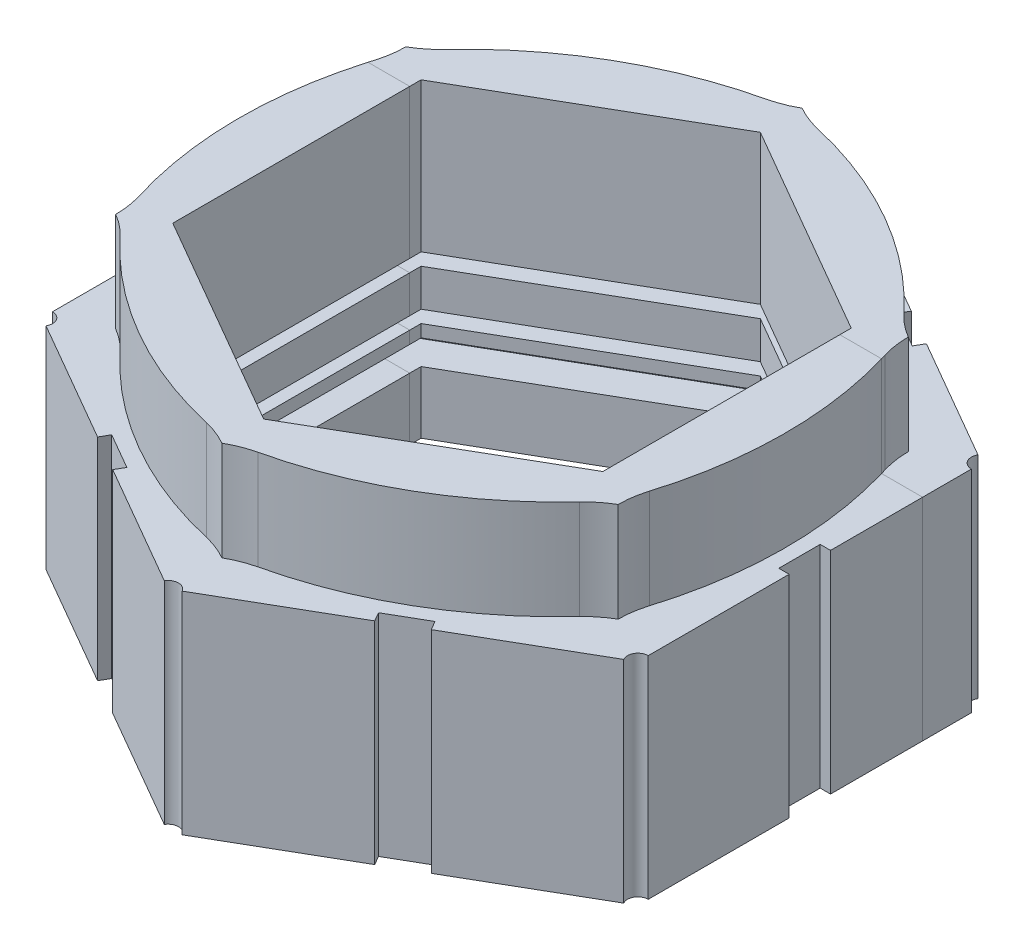
SolidWorks part; units mm, degrees
ref_plane "Front Plane" through (0, 0, 0) normal (0, 0, 1) x (1, 0, 0)
ref_plane "Top Plane" through (0, 0, 0) normal (0, 1, 0) x (1, 0, 0)
ref_plane "Right Plane" through (0, 0, 0) normal (1, 0, 0) x (0, 0, -1)
sketch "Sketch1" plane through (0, 0, 0) normal (0, 1, 0) x (1, 0, 0)
  line L0 (0, 83.094) -> (-71.9615, 41.547)
  line L1 (0, 60) -> (-51.9615, 30)
  line L2 (-51.9615, 30) -> (-51.9615, -30)
  line L3 (-51.9615, -30) -> (0, -60)
  line L4 (0, -60) -> (51.9615, -30)
  line L5 (51.9615, -30) -> (51.9615, 30)
  line L6 (51.9615, 30) -> (0, 60)
  line L7 (-71.9615, 41.547) -> (-71.9615, -41.547)
  line L8 (-71.9615, -41.547) -> (0, -83.094)
  line L9 (0, -83.094) -> (71.9615, -41.547)
  line L10 (71.9615, -41.547) -> (71.9615, 41.547)
  line L11 (71.9615, 41.547) -> (0, 83.094)
  circle A0 centre (0, 0) radius 60 construction
  dimension "D1" = 120
  dimension "D3" = 83.094
  dimension "D2" = 20
extrude "top xtra thick" add sketch "Sketch1" along normal blind 9
sketch "pattern cutout" plane through (0, 9, 0) normal (0, 1, 0) x (1, 0, 0)
  line L0 (38.9808, 67.5167) -> (21.1536, 77.8092) construction
  line L7 (71.9615, 41.547) -> (0, 83.094) construction
  line L8 (51.9615, 30) -> (0, 60) construction
  line L9 (32.9808, 57.1244) -> (38.9808, 67.5167) construction
  line L10 (22.5167, 70.094) -> (35.9808, 62.3205) construction
  line L12 (40.756, 100.3003) -> (40.756, 88.3003) construction
  line L13 (0, 83.094) -> (0, 60) construction
  line L14 (0, 109.094) -> (-22.5167, 70.094) construction
  line L15 (-22.5167, 70.094) -> (22.5167, 70.094) construction
  line L16 (22.5167, 70.094) -> (0, 109.094) construction
  line L18 (32.9808, 57.1244) -> (15.1536, 67.4168) construction
  line L19 (-32.9808, 57.1244) -> (-38.9808, 67.5167) construction
  line L20 (-32.9808, 57.1244) -> (-15.1536, 67.4168) construction
  line L21 (-22.5167, 70.094) -> (-35.9808, 62.3205) construction
  line L22 (-38.9808, 67.5167) -> (-21.1536, 77.8092) construction
  line L23 (-6, 124.641) -> (-6, 104.056) construction
  line L24 (0, 109.094) -> (0, 124.641) construction
  line L25 (6, 124.641) -> (6, 104.056) construction
  line L26 (0, 83.094) -> (6.2183, 67.6487) construction
  line L27 (0, 83.094) -> (10.2669, 96.2019) construction
  circle A0 centre (0, 83.094) radius 13 construction
  arc A1 (0, 109.094) -> (-11.2583, 89.594) centre (11.2583, 89.594) ccw
  arc A2 (-6.2183, 67.6487) -> (0, 70.094) centre (-11.2583, 89.594) ccw
  arc A3 (16.4852, 85.4315) -> (11.2583, 89.594) centre (0, 70.094) ccw
  arc A4 (16.4852, 85.4315) -> (38.9808, 67.5167) centre (87.4345, 151.441) ccw
  arc A5 (6.2183, 67.6487) -> (32.9808, 57.1244) centre (-15.473, -26.7999) cw
  arc A6 (-6.2183, 67.6487) -> (-32.9808, 57.1244) centre (15.473, -26.7999) ccw
  arc A7 (-16.4852, 85.4315) -> (-38.9808, 67.5167) centre (-87.4345, 151.441) cw
  arc A8 (-21.1536, 77.8092) -> (-22.5167, 70.094) centre (0, 70.094) ccw construction
  arc A9 (-16.4852, 85.4315) -> (-21.1536, 77.8092) centre (0, 70.094) ccw construction
  arc A10 (-22.5167, 70.094) -> (-15.1536, 67.4168) centre (-11.2583, 89.594) ccw construction
  arc A11 (-15.1536, 67.4168) -> (-6.2183, 67.6487) centre (-11.2583, 89.594) ccw construction
  arc A12 (15.1536, 67.4168) -> (22.5167, 70.094) centre (11.2583, 89.594) ccw construction
  arc A13 (6.2183, 67.6487) -> (15.1536, 67.4168) centre (11.2583, 89.594) ccw construction
  arc A14 (22.5167, 70.094) -> (21.1536, 77.8092) centre (0, 70.094) ccw construction
  arc A15 (21.1536, 77.8092) -> (16.4852, 85.4315) centre (0, 70.094) ccw construction
  arc A16 (0, 70.094) -> (6.2183, 67.6487) centre (11.2583, 89.594) ccw
  arc A17 (-11.2583, 89.594) -> (0, 70.094) centre (11.2583, 89.594) ccw construction
  arc A18 (-11.2583, 89.594) -> (-16.4852, 85.4315) centre (0, 70.094) ccw
  arc A19 (11.2583, 89.594) -> (-11.2583, 89.594) centre (0, 70.094) ccw construction
  arc A20 (11.2583, 89.594) -> (0, 109.094) centre (-11.2583, 89.594) ccw
  arc A21 (0, 70.094) -> (11.2583, 89.594) centre (-11.2583, 89.594) ccw construction
  arc A22 (-10.2669, 96.2019) -> (-6, 124.641) centre (-102.9074, 124.641) ccw
  arc A23 (10.2669, 96.2019) -> (6, 124.641) centre (102.9074, 124.641) cw
  arc A24 (55.4763, 39.2096) -> (32.9808, 57.1244) centre (-15.473, -26.7999) ccw
  arc A25 (65.7432, 56.9924) -> (38.9808, 67.5167) centre (87.4345, 151.441) cw
  arc A26 (71.9615, 54.547) -> (65.7432, 56.9924) centre (60.7032, 35.047) ccw
  arc A27 (94.4782, 54.547) -> (71.9615, 54.547) centre (83.2199, 35.047) ccw
  arc A28 (83.2199, 35.047) -> (94.4782, 54.547) centre (71.9615, 54.547) ccw
  arc A29 (82.2284, 28.4391) -> (83.2199, 35.047) centre (60.7032, 35.047) ccw
  arc A30 (82.2284, 28.4391) -> (77.9615, 0) centre (174.869, 0) ccw
  arc A31 (61.6946, 28.4391) -> (65.9615, 0) centre (-30.9459, 0) cw
  arc A32 (60.7032, 35.047) -> (61.6946, 28.4391) centre (83.2199, 35.047) ccw
  arc A33 (55.4763, 39.2096) -> (60.7032, 35.047) centre (71.9615, 54.547) ccw
  arc A34 (78.1798, 56.9924) -> (104.9423, 67.5167) centre (56.4886, 151.441) ccw
  arc A35 (88.4467, 39.2096) -> (110.9423, 57.1244) centre (159.396, -26.7999) cw
  arc A36 (61.6946, -28.4391) -> (65.9615, 0) centre (-30.9459, 0) ccw
  arc A37 (82.2284, -28.4391) -> (77.9615, 0) centre (174.869, 0) cw
  arc A38 (83.2199, -35.047) -> (82.2284, -28.4391) centre (60.7032, -35.047) ccw
  arc A39 (94.4782, -54.547) -> (83.2199, -35.047) centre (71.9615, -54.547) ccw
  arc A40 (71.9615, -54.547) -> (94.4782, -54.547) centre (83.2199, -35.047) ccw
  arc A41 (65.7432, -56.9924) -> (71.9615, -54.547) centre (60.7032, -35.047) ccw
  arc A42 (65.7432, -56.9924) -> (38.9808, -67.5167) centre (87.4345, -151.441) ccw
  arc A43 (55.4763, -39.2096) -> (32.9808, -57.1244) centre (-15.473, 26.7999) cw
  arc A44 (60.7032, -35.047) -> (55.4763, -39.2096) centre (71.9615, -54.547) ccw
  arc A45 (61.6946, -28.4391) -> (60.7032, -35.047) centre (83.2199, -35.047) ccw
  arc A46 (88.4467, -39.2096) -> (110.9423, -57.1244) centre (159.396, 26.7999) ccw
  arc A47 (78.1798, -56.9924) -> (104.9423, -67.5167) centre (56.4886, -151.441) cw
  arc A48 (6.2183, -67.6487) -> (32.9808, -57.1244) centre (-15.473, 26.7999) ccw
  arc A49 (16.4852, -85.4315) -> (38.9808, -67.5167) centre (87.4345, -151.441) cw
  arc A50 (11.2583, -89.594) -> (16.4852, -85.4315) centre (0, -70.094) ccw
  arc A51 (0, -109.094) -> (11.2583, -89.594) centre (-11.2583, -89.594) ccw
  arc A52 (-11.2583, -89.594) -> (0, -109.094) centre (11.2583, -89.594) ccw
  arc A53 (-16.4852, -85.4315) -> (-11.2583, -89.594) centre (0, -70.094) ccw
  arc A54 (-16.4852, -85.4315) -> (-38.9808, -67.5167) centre (-87.4345, -151.441) ccw
  arc A55 (-6.2183, -67.6487) -> (-32.9808, -57.1244) centre (15.473, 26.7999) cw
  arc A56 (0, -70.094) -> (-6.2183, -67.6487) centre (-11.2583, -89.594) ccw
  arc A57 (6.2183, -67.6487) -> (0, -70.094) centre (11.2583, -89.594) ccw
  arc A58 (10.2669, -96.2019) -> (6, -124.641) centre (102.9074, -124.641) ccw
  arc A59 (-10.2669, -96.2019) -> (-6, -124.641) centre (-102.9074, -124.641) cw
  arc A60 (-55.4763, -39.2096) -> (-32.9808, -57.1244) centre (15.473, 26.7999) ccw
  arc A61 (-65.7432, -56.9924) -> (-38.9808, -67.5167) centre (-87.4345, -151.441) cw
  arc A62 (-71.9615, -54.547) -> (-65.7432, -56.9924) centre (-60.7032, -35.047) ccw
  arc A63 (-94.4782, -54.547) -> (-71.9615, -54.547) centre (-83.2199, -35.047) ccw
  arc A64 (-83.2199, -35.047) -> (-94.4782, -54.547) centre (-71.9615, -54.547) ccw
  arc A65 (-82.2284, -28.4391) -> (-83.2199, -35.047) centre (-60.7032, -35.047) ccw
  arc A66 (-82.2284, -28.4391) -> (-77.9615, 0) centre (-174.869, 0) ccw
  arc A67 (-61.6946, -28.4391) -> (-65.9615, 0) centre (30.9459, 0) cw
  arc A68 (-60.7032, -35.047) -> (-61.6946, -28.4391) centre (-83.2199, -35.047) ccw
  arc A69 (-55.4763, -39.2096) -> (-60.7032, -35.047) centre (-71.9615, -54.547) ccw
  arc A70 (-78.1798, -56.9924) -> (-104.9423, -67.5167) centre (-56.4886, -151.441) ccw
  arc A71 (-88.4467, -39.2096) -> (-110.9423, -57.1244) centre (-159.396, 26.7999) cw
  arc A72 (-61.6946, 28.4391) -> (-65.9615, 0) centre (30.9459, 0) ccw
  arc A73 (-82.2284, 28.4391) -> (-77.9615, 0) centre (-174.869, 0) cw
  arc A74 (-83.2199, 35.047) -> (-82.2284, 28.4391) centre (-60.7032, 35.047) ccw
  arc A75 (-94.4782, 54.547) -> (-83.2199, 35.047) centre (-71.9615, 54.547) ccw
  arc A76 (-71.9615, 54.547) -> (-94.4782, 54.547) centre (-83.2199, 35.047) ccw
  arc A77 (-65.7432, 56.9924) -> (-71.9615, 54.547) centre (-60.7032, 35.047) ccw
  arc A78 (-65.7432, 56.9924) -> (-38.9808, 67.5167) centre (-87.4345, 151.441) ccw
  arc A79 (-55.4763, 39.2096) -> (-32.9808, 57.1244) centre (15.473, -26.7999) cw
  arc A80 (-60.7032, 35.047) -> (-55.4763, 39.2096) centre (-71.9615, 54.547) ccw
  arc A81 (-61.6946, 28.4391) -> (-60.7032, 35.047) centre (-83.2199, 35.047) ccw
  arc A82 (-88.4467, 39.2096) -> (-110.9423, 57.1244) centre (-159.396, -26.7999) ccw
  arc A83 (-78.1798, 56.9924) -> (-104.9423, 67.5167) centre (-56.4886, 151.441) cw
  point P158 (0, 0)
  line M1 (71.9615, 41.547) -> (0, 83.094)
  line M2 (0, 83.094) -> (-71.9615, 41.547)
  line M3 (-71.9615, 41.547) -> (-71.9615, -41.547)
  line M4 (-71.9615, -41.547) -> (0, -83.094)
  line M5 (0, -83.094) -> (71.9615, -41.547)
  line M6 (71.9615, -41.547) -> (71.9615, 41.547)
  dimension "D1" = 26
  dimension "D2" = 2
  dimension "D3" = 12
  dimension "D4" = 120
  dimension "D5" = 6
sketch "Sketch4" plane through (0, 9, 0) normal (0, 1, 0) x (1, 0, 0)
  line L0 (-51.9615, -30) -> (0, -60) construction
  line L1 (0, -60) -> (51.9615, -30) construction
  line L2 (51.9615, -30) -> (51.9615, 30) construction
  line L3 (51.9615, 30) -> (0, 60) construction
  line L4 (0, 60) -> (-51.9615, 30) construction
  line L5 (-51.9615, 30) -> (-51.9615, -30) construction
  line L6 (71.9615, 41.547) -> (0, 83.094)
  line L7 (0, 83.094) -> (-71.9615, 41.547)
  line L8 (-71.9615, 41.547) -> (-71.9615, -41.547)
  line L9 (-71.9615, -41.547) -> (0, -83.094)
  line L10 (0, -83.094) -> (71.9615, -41.547)
  line L11 (71.9615, -41.547) -> (71.9615, 41.547)
  line L12 (71.9615, 41.547) -> (0, 83.094)
  line L13 (0, 83.094) -> (-71.9615, 41.547)
  line L14 (-71.9615, 41.547) -> (-71.9615, -41.547)
  line L15 (-71.9615, -41.547) -> (0, -83.094)
  line L16 (0, -83.094) -> (71.9615, -41.547)
  line L17 (71.9615, -41.547) -> (71.9615, 41.547)
  line L18 (-51.9615, -30) -> (0, -60)
  line L19 (0, -60) -> (51.9615, -30)
  line L20 (51.9615, -30) -> (51.9615, 30)
  line L21 (51.9615, 30) -> (0, 60)
  line L22 (0, 60) -> (-51.9615, 30)
  line L23 (-51.9615, 30) -> (-51.9615, -30)
  dimension "D1" = 0
extrude "Boss-Extrude3" add sketch "Sketch4" along normal blind 24
extrude "Cut-Extrude4" cut sketch "pattern cutout" along normal up to surface (24 mm away) contours M1 M6 | M6 M1 M2 M3 M4 M5 region at (4.0975, 9, -101.823) region at (69.7631, 9, 0) up to face at (0, 33, 0)
sketch "Sketch5" plane through (0, 9, 0) normal (0, 1, 0) x (1, 0, 0)
  circle A0 centre (0, 83.094) radius 2.5
  circle A1 centre (71.9615, 41.547) radius 2.5
  circle A2 centre (71.9615, -41.547) radius 2.5
  circle A3 centre (0, -83.094) radius 2.5
  circle A4 centre (-71.9615, -41.547) radius 2.5
  circle A5 centre (-71.9615, 41.547) radius 2.5
  point P15 (0, 0)
  dimension "D1" = 5
  dimension "D2" = 6
extrude "house wirehole" cut sketch "Sketch5" against normal blind 50
sketch "Sketch6" plane through (0, 9, 0) normal (0, 1, 0) x (1, 0, 0)
  line L0 (-69.4615, 5) -> (-69.4615, -5)
  line L1 (-69.4615, 5) -> (-74.4615, 5)
  line L2 (-69.4615, -5) -> (-74.4615, -5)
  line L3 (-74.4615, 5) -> (-74.4615, -5)
  line L4 (-69.4615, 5) -> (-74.4615, -5) construction
  line L5 (-69.4615, -5) -> (-74.4615, 5) construction
  line L6 (-71.9615, 39.047) -> (-71.9615, -39.047) construction
  line L7 (-32.9006, 66.9856) -> (-41.5609, 61.9856)
  line L8 (-30.4006, 62.6554) -> (-32.9006, 66.9856)
  line L9 (-30.4006, 62.6554) -> (-39.0609, 57.6554)
  line L10 (-39.0609, 57.6554) -> (-41.5609, 61.9856)
  line L11 (41.5609, 61.9856) -> (32.9006, 66.9856)
  line L12 (39.0609, 57.6554) -> (41.5609, 61.9856)
  line L13 (39.0609, 57.6554) -> (30.4006, 62.6554)
  line L14 (30.4006, 62.6554) -> (32.9006, 66.9856)
  line L15 (74.4615, -5) -> (74.4615, 5)
  line L16 (69.4615, -5) -> (74.4615, -5)
  line L17 (69.4615, -5) -> (69.4615, 5)
  line L18 (69.4615, 5) -> (74.4615, 5)
  line L19 (32.9006, -66.9856) -> (41.5609, -61.9856)
  line L20 (30.4006, -62.6554) -> (32.9006, -66.9856)
  line L21 (30.4006, -62.6554) -> (39.0609, -57.6554)
  line L22 (39.0609, -57.6554) -> (41.5609, -61.9856)
  line L23 (-41.5609, -61.9856) -> (-32.9006, -66.9856)
  line L24 (-39.0609, -57.6554) -> (-41.5609, -61.9856)
  line L25 (-39.0609, -57.6554) -> (-30.4006, -62.6554)
  line L26 (-30.4006, -62.6554) -> (-32.9006, -66.9856)
  point P1 (-71.9615, 0)
  point P6 (-35.9808, 62.3205)
  point P15 (35.9808, 62.3205)
  point P20 (71.9615, 0)
  point P25 (35.9808, -62.3205)
  point P30 (-35.9808, -62.3205)
  dimension "D1" = 5
  dimension "D2" = 10
  dimension "D3" = 6
extrude "road wireholes" cut sketch "Sketch6" against normal blind 50
sketch "Sketch7" plane through (0, 0, 0) normal (0, -1, 0) x (1, 0, 0)
  line L0 (0, -69.2376) -> (59.9615, -34.6188)
  line L1 (59.9615, -34.6188) -> (59.9615, 34.6188)
  line L2 (59.9615, 34.6188) -> (0, 69.2376)
  line L3 (0, 69.2376) -> (-59.9615, 34.6188)
  line L4 (-59.9615, 34.6188) -> (-59.9615, -34.6188)
  line L5 (-59.9615, -34.6188) -> (0, -69.2376)
  line L6 (0, -60) -> (51.9615, -30)
  line L7 (-51.9615, -30) -> (0, -60)
  line L8 (-51.9615, 30) -> (-51.9615, -30)
  line L9 (0, 60) -> (-51.9615, 30)
  line L10 (51.9615, 30) -> (0, 60)
  line L11 (51.9615, -30) -> (51.9615, 30)
  line L12 (0, -60) -> (51.9615, -30) construction
  line L13 (-51.9615, -30) -> (0, -60) construction
  line L14 (-51.9615, 30) -> (-51.9615, -30) construction
  line L15 (0, 60) -> (-51.9615, 30) construction
  line L16 (51.9615, 30) -> (0, 60) construction
  line L17 (51.9615, -30) -> (51.9615, 30) construction
  line L48 (69.7965, 42.797) -> (40.3109, 59.8205)
  line L49 (40.3109, 59.8205) -> (39.0609, 57.6554)
  line L50 (40.3109, 59.8205) -> (39.0609, 57.6554)
  line L51 (39.0609, 57.6554) -> (30.4006, 62.6554)
  line L52 (39.0609, 57.6554) -> (30.4006, 62.6554)
  line L53 (-2.1651, 81.844) -> (-31.6506, 64.8205)
  line L54 (30.4006, 62.6554) -> (31.6506, 64.8205)
  line L55 (30.4006, 62.6554) -> (31.6506, 64.8205)
  line L56 (31.6506, 64.8205) -> (2.1651, 81.844)
  line L57 (31.6506, 64.8205) -> (2.1651, 81.844)
  line L58 (-71.9615, 39.047) -> (-71.9615, 5)
  line L59 (-31.6506, 64.8205) -> (-30.4006, 62.6554)
  line L60 (-31.6506, 64.8205) -> (-30.4006, 62.6554)
  line L61 (-30.4006, 62.6554) -> (-39.0609, 57.6554)
  line L62 (-30.4006, 62.6554) -> (-39.0609, 57.6554)
  line L63 (-69.7965, -42.797) -> (-40.3109, -59.8205)
  line L64 (-39.0609, 57.6554) -> (-40.3109, 59.8205)
  line L65 (-39.0609, 57.6554) -> (-40.3109, 59.8205)
  line L66 (-40.3109, 59.8205) -> (-69.7965, 42.797)
  line L67 (-40.3109, 59.8205) -> (-69.7965, 42.797)
  line L68 (2.1651, -81.844) -> (31.6506, -64.8205)
  line L69 (-71.9615, 5) -> (-69.4615, 5)
  line L70 (-71.9615, 5) -> (-69.4615, 5)
  line L71 (-69.4615, 5) -> (-69.4615, -5)
  line L72 (-69.4615, 5) -> (-69.4615, -5)
  line L73 (71.9615, -39.047) -> (71.9615, -5)
  line L74 (-69.4615, -5) -> (-71.9615, -5)
  line L75 (-69.4615, -5) -> (-71.9615, -5)
  line L76 (-71.9615, -5) -> (-71.9615, -39.047)
  line L77 (-71.9615, -5) -> (-71.9615, -39.047)
  line L78 (69.7965, 42.797) -> (40.3109, 59.8205)
  line L83 (-2.1651, 81.844) -> (-31.6506, 64.8205)
  line L88 (-71.9615, 39.047) -> (-71.9615, 5)
  line L93 (-69.7965, -42.797) -> (-40.3109, -59.8205)
  line L98 (2.1651, -81.844) -> (31.6506, -64.8205)
  line L103 (71.9615, -39.047) -> (71.9615, -5)
  line L108 (-40.3109, -59.8205) -> (-39.0609, -57.6554)
  line L109 (-40.3109, -59.8205) -> (-39.0609, -57.6554)
  line L110 (-39.0609, -57.6554) -> (-30.4006, -62.6554)
  line L111 (-39.0609, -57.6554) -> (-30.4006, -62.6554)
  line L112 (-30.4006, -62.6554) -> (-31.6506, -64.8205)
  line L113 (-30.4006, -62.6554) -> (-31.6506, -64.8205)
  line L114 (-31.6506, -64.8205) -> (-2.1651, -81.844)
  line L115 (-31.6506, -64.8205) -> (-2.1651, -81.844)
  line L116 (31.6506, -64.8205) -> (30.4006, -62.6554)
  line L117 (31.6506, -64.8205) -> (30.4006, -62.6554)
  line L118 (30.4006, -62.6554) -> (39.0609, -57.6554)
  line L119 (30.4006, -62.6554) -> (39.0609, -57.6554)
  line L120 (39.0609, -57.6554) -> (40.3109, -59.8205)
  line L121 (39.0609, -57.6554) -> (40.3109, -59.8205)
  line L122 (40.3109, -59.8205) -> (69.7965, -42.797)
  line L123 (40.3109, -59.8205) -> (69.7965, -42.797)
  line L124 (71.9615, -5) -> (69.4615, -5)
  line L125 (71.9615, -5) -> (69.4615, -5)
  line L126 (69.4615, -5) -> (69.4615, 5)
  line L127 (69.4615, -5) -> (69.4615, 5)
  line L128 (69.4615, 5) -> (71.9615, 5)
  line L129 (69.4615, 5) -> (71.9615, 5)
  line L130 (71.9615, 5) -> (71.9615, 39.047)
  line L131 (71.9615, 5) -> (71.9615, 39.047)
  arc A6 (-2.1651, 81.844) -> (2.1651, 81.844) centre (0, 83.094) ccw
  arc A7 (-2.1651, 81.844) -> (2.1651, 81.844) centre (0, 83.094) ccw
  arc A8 (-71.9615, 39.047) -> (-69.7965, 42.797) centre (-71.9615, 41.547) ccw
  arc A9 (-71.9615, 39.047) -> (-69.7965, 42.797) centre (-71.9615, 41.547) ccw
  arc A10 (-69.7965, -42.797) -> (-71.9615, -39.047) centre (-71.9615, -41.547) ccw
  arc A11 (-69.7965, -42.797) -> (-71.9615, -39.047) centre (-71.9615, -41.547) ccw
  arc A18 (2.1651, -81.844) -> (-2.1651, -81.844) centre (0, -83.094) ccw
  arc A19 (2.1651, -81.844) -> (-2.1651, -81.844) centre (0, -83.094) ccw
  arc A20 (71.9615, -39.047) -> (69.7965, -42.797) centre (71.9615, -41.547) ccw
  arc A21 (71.9615, -39.047) -> (69.7965, -42.797) centre (71.9615, -41.547) ccw
  arc A22 (69.7965, 42.797) -> (71.9615, 39.047) centre (71.9615, 41.547) ccw
  arc A23 (69.7965, 42.797) -> (71.9615, 39.047) centre (71.9615, 41.547) ccw
  dimension "D1" = 0
  dimension "D2" = 8
  dimension "D3" = 0
extrude "8mm notch" add sketch "Sketch7" along normal blind 9
sketch "Sketch9" plane through (0, 0, 0) normal (0, -1, 0) x (1, 0, 0)
  line L0 (-59.9615, 34.6188) -> (-59.9615, -34.6188) construction
  line L1 (-59.9615, 12.5) -> (-56.9615, 12.5)
  line L2 (-59.9615, 12.5) -> (-59.9615, -12.5)
  line L3 (-59.9615, -12.5) -> (-56.9615, -12.5)
  line L4 (-56.9615, 12.5) -> (-56.9615, -12.5)
  line L5 (-19.1554, 58.1782) -> (-17.6554, 55.5801)
  line L6 (-19.1554, 58.1782) -> (-40.8061, 45.6782)
  line L7 (-40.8061, 45.6782) -> (-39.3061, 43.0801)
  line L8 (-17.6554, 55.5801) -> (-39.3061, 43.0801)
  line L9 (40.8061, 45.6782) -> (39.3061, 43.0801)
  line L10 (40.8061, 45.6782) -> (19.1554, 58.1782)
  line L11 (19.1554, 58.1782) -> (17.6554, 55.5801)
  line L12 (39.3061, 43.0801) -> (17.6554, 55.5801)
  line L13 (59.9615, -12.5) -> (56.9615, -12.5)
  line L14 (59.9615, -12.5) -> (59.9615, 12.5)
  line L15 (59.9615, 12.5) -> (56.9615, 12.5)
  line L16 (56.9615, -12.5) -> (56.9615, 12.5)
  line L17 (19.1554, -58.1782) -> (17.6554, -55.5801)
  line L18 (19.1554, -58.1782) -> (40.8061, -45.6782)
  line L19 (40.8061, -45.6782) -> (39.3061, -43.0801)
  line L20 (17.6554, -55.5801) -> (39.3061, -43.0801)
  line L21 (-40.8061, -45.6782) -> (-39.3061, -43.0801)
  line L22 (-40.8061, -45.6782) -> (-19.1554, -58.1782)
  line L23 (-19.1554, -58.1782) -> (-17.6554, -55.5801)
  line L24 (-39.3061, -43.0801) -> (-17.6554, -55.5801)
  point P6 (-59.9615, 0)
  point P29 (0, 0)
  line M5 (-59.9615, -34.6188) -> (0, -69.2376)
  line M6 (0, -69.2376) -> (59.9615, -34.6188)
  line M7 (59.9615, -34.6188) -> (59.9615, 34.6188)
  line M8 (59.9615, 34.6188) -> (0, 69.2376)
  line M9 (0, 69.2376) -> (-59.9615, 34.6188)
  dimension "D1" = 25
  dimension "D2" = 3
  dimension "D3" = 6
extrude "LED spacemakers" cut sketch "Sketch9" against normal blind 3 contours L8 L5 L7 M9 | L12 L9 L11 M8 | L16 L13 L15 M7 | L20 L17 L19 M6 | L24 L21 L23 M5 | L4 L3 L2 L1 region at (-29.2308, 0, 50.6292) region at (-29.2308, 0, -50.6292) region at (29.2308, 0, -50.6292) region at (58.4615, 0, 0) region at (29.2308, 0, 50.6292)
sketch "Sketch10" plane through (0, -9, 0) normal (0, -1, 0) x (1, 0, 0)
  line L6 (0, -60) -> (51.9615, -30)
  line L7 (-51.9615, -30) -> (0, -60)
  line L8 (-51.9615, 30) -> (-51.9615, -30)
  line L9 (0, 60) -> (-51.9615, 30)
  line L10 (51.9615, 30) -> (0, 60)
  line L11 (51.9615, -30) -> (51.9615, 30)
  line L12 (0, -60) -> (51.9615, -30)
  line L13 (-51.9615, -30) -> (0, -60)
  line L14 (-51.9615, 30) -> (-51.9615, -30)
  line L15 (0, 60) -> (-51.9615, 30)
  line L16 (51.9615, 30) -> (0, 60)
  line L17 (51.9615, -30) -> (51.9615, 30)
  line L30 (-59.9615, 12.5) -> (-56.9615, 12.5)
  line L31 (-56.9615, 12.5) -> (-56.9615, -12.5)
  line L32 (-56.9615, -12.5) -> (-59.9615, -12.5)
  line L33 (-59.9615, -12.5) -> (-59.9615, -34.6188)
  line L34 (-59.9615, -34.6188) -> (-40.8061, -45.6782)
  line L35 (-40.8061, -45.6782) -> (-39.3061, -43.0801)
  line L36 (-39.3061, -43.0801) -> (-17.6554, -55.5801)
  line L37 (-17.6554, -55.5801) -> (-19.1554, -58.1782)
  line L38 (-19.1554, -58.1782) -> (0, -69.2376)
  line L39 (0, -69.2376) -> (19.1554, -58.1782)
  line L40 (19.1554, -58.1782) -> (17.6554, -55.5801)
  line L41 (17.6554, -55.5801) -> (39.3061, -43.0801)
  line L42 (39.3061, -43.0801) -> (40.8061, -45.6782)
  line L43 (40.8061, -45.6782) -> (59.9615, -34.6188)
  line L44 (59.9615, -34.6188) -> (59.9615, -12.5)
  line L45 (59.9615, -12.5) -> (56.9615, -12.5)
  line L46 (56.9615, -12.5) -> (56.9615, 12.5)
  line L47 (56.9615, 12.5) -> (59.9615, 12.5)
  line L48 (59.9615, 12.5) -> (59.9615, 34.6188)
  line L49 (59.9615, 34.6188) -> (40.8061, 45.6782)
  line L50 (40.8061, 45.6782) -> (39.3061, 43.0801)
  line L51 (39.3061, 43.0801) -> (17.6554, 55.5801)
  line L52 (17.6554, 55.5801) -> (19.1554, 58.1782)
  line L53 (19.1554, 58.1782) -> (0, 69.2376)
  line L54 (0, 69.2376) -> (-19.1554, 58.1782)
  line L55 (-19.1554, 58.1782) -> (-17.6554, 55.5801)
  line L56 (-17.6554, 55.5801) -> (-39.3061, 43.0801)
  line L57 (-39.3061, 43.0801) -> (-40.8061, 45.6782)
  line L58 (-40.8061, 45.6782) -> (-59.9615, 34.6188)
  line L59 (-59.9615, 34.6188) -> (-59.9615, 12.5)
  line L60 (-59.9615, 12.5) -> (-56.9615, 12.5)
  line L61 (-56.9615, 12.5) -> (-56.9615, -12.5)
  line L62 (-56.9615, -12.5) -> (-59.9615, -12.5)
  line L63 (-59.9615, -12.5) -> (-59.9615, -34.6188)
  line L64 (-59.9615, -34.6188) -> (-40.8061, -45.6782)
  line L65 (-40.8061, -45.6782) -> (-39.3061, -43.0801)
  line L66 (-39.3061, -43.0801) -> (-17.6554, -55.5801)
  line L67 (-17.6554, -55.5801) -> (-19.1554, -58.1782)
  line L68 (-19.1554, -58.1782) -> (0, -69.2376)
  line L69 (0, -69.2376) -> (19.1554, -58.1782)
  line L70 (19.1554, -58.1782) -> (17.6554, -55.5801)
  line L71 (17.6554, -55.5801) -> (39.3061, -43.0801)
  line L72 (39.3061, -43.0801) -> (40.8061, -45.6782)
  line L73 (40.8061, -45.6782) -> (59.9615, -34.6188)
  line L74 (59.9615, -34.6188) -> (59.9615, -12.5)
  line L75 (59.9615, -12.5) -> (56.9615, -12.5)
  line L76 (56.9615, -12.5) -> (56.9615, 12.5)
  line L77 (56.9615, 12.5) -> (59.9615, 12.5)
  line L78 (59.9615, 12.5) -> (59.9615, 34.6188)
  line L79 (59.9615, 34.6188) -> (40.8061, 45.6782)
  line L80 (40.8061, 45.6782) -> (39.3061, 43.0801)
  line L81 (39.3061, 43.0801) -> (17.6554, 55.5801)
  line L82 (17.6554, 55.5801) -> (19.1554, 58.1782)
  line L83 (19.1554, 58.1782) -> (0, 69.2376)
  line L84 (0, 69.2376) -> (-19.1554, 58.1782)
  line L85 (-19.1554, 58.1782) -> (-17.6554, 55.5801)
  line L86 (-17.6554, 55.5801) -> (-39.3061, 43.0801)
  line L87 (-39.3061, 43.0801) -> (-40.8061, 45.6782)
  line L88 (-40.8061, 45.6782) -> (-59.9615, 34.6188)
  line L89 (-59.9615, 34.6188) -> (-59.9615, 12.5)
  line L102 (39.0609, 57.6554) -> (30.4006, 62.6554)
  line L103 (30.4006, 62.6554) -> (31.6506, 64.8205)
  line L104 (31.6506, 64.8205) -> (2.1651, 81.844)
  line L105 (-2.1651, 81.844) -> (-31.6506, 64.8205)
  line L106 (-31.6506, 64.8205) -> (-30.4006, 62.6554)
  line L107 (-30.4006, 62.6554) -> (-39.0609, 57.6554)
  line L108 (-39.0609, 57.6554) -> (-40.3109, 59.8205)
  line L109 (-40.3109, 59.8205) -> (-69.7965, 42.797)
  line L110 (-71.9615, 39.047) -> (-71.9615, 5)
  line L111 (-71.9615, 5) -> (-69.4615, 5)
  line L112 (-69.4615, 5) -> (-69.4615, -5)
  line L113 (-69.4615, -5) -> (-71.9615, -5)
  line L114 (-71.9615, -5) -> (-71.9615, -39.047)
  line L115 (-69.7965, -42.797) -> (-40.3109, -59.8205)
  line L116 (-40.3109, -59.8205) -> (-39.0609, -57.6554)
  line L117 (-39.0609, -57.6554) -> (-30.4006, -62.6554)
  line L118 (-30.4006, -62.6554) -> (-31.6506, -64.8205)
  line L119 (-31.6506, -64.8205) -> (-2.1651, -81.844)
  line L120 (2.1651, -81.844) -> (31.6506, -64.8205)
  line L121 (31.6506, -64.8205) -> (30.4006, -62.6554)
  line L122 (30.4006, -62.6554) -> (39.0609, -57.6554)
  line L123 (39.0609, -57.6554) -> (40.3109, -59.8205)
  line L124 (40.3109, -59.8205) -> (69.7965, -42.797)
  line L125 (71.9615, -39.047) -> (71.9615, -5)
  line L126 (71.9615, -5) -> (69.4615, -5)
  line L127 (69.4615, -5) -> (69.4615, 5)
  line L128 (69.4615, 5) -> (71.9615, 5)
  line L129 (71.9615, 5) -> (71.9615, 39.047)
  line L130 (69.7965, 42.797) -> (40.3109, 59.8205)
  line L131 (40.3109, 59.8205) -> (39.0609, 57.6554)
  line L132 (39.0609, 57.6554) -> (30.4006, 62.6554)
  line L133 (30.4006, 62.6554) -> (31.6506, 64.8205)
  line L134 (31.6506, 64.8205) -> (2.1651, 81.844)
  line L135 (-2.1651, 81.844) -> (-31.6506, 64.8205)
  line L136 (-31.6506, 64.8205) -> (-30.4006, 62.6554)
  line L137 (-30.4006, 62.6554) -> (-39.0609, 57.6554)
  line L138 (-39.0609, 57.6554) -> (-40.3109, 59.8205)
  line L139 (-40.3109, 59.8205) -> (-69.7965, 42.797)
  line L140 (-71.9615, 39.047) -> (-71.9615, 5)
  line L141 (-71.9615, 5) -> (-69.4615, 5)
  line L142 (-69.4615, 5) -> (-69.4615, -5)
  line L143 (-69.4615, -5) -> (-71.9615, -5)
  line L144 (-71.9615, -5) -> (-71.9615, -39.047)
  line L145 (-69.7965, -42.797) -> (-40.3109, -59.8205)
  line L146 (-40.3109, -59.8205) -> (-39.0609, -57.6554)
  line L147 (-39.0609, -57.6554) -> (-30.4006, -62.6554)
  line L148 (-30.4006, -62.6554) -> (-31.6506, -64.8205)
  line L149 (-31.6506, -64.8205) -> (-2.1651, -81.844)
  line L150 (2.1651, -81.844) -> (31.6506, -64.8205)
  line L151 (31.6506, -64.8205) -> (30.4006, -62.6554)
  line L152 (30.4006, -62.6554) -> (39.0609, -57.6554)
  line L153 (39.0609, -57.6554) -> (40.3109, -59.8205)
  line L154 (40.3109, -59.8205) -> (69.7965, -42.797)
  line L155 (71.9615, -39.047) -> (71.9615, -5)
  line L156 (71.9615, -5) -> (69.4615, -5)
  line L157 (69.4615, -5) -> (69.4615, 5)
  line L158 (69.4615, 5) -> (71.9615, 5)
  line L159 (71.9615, 5) -> (71.9615, 39.047)
  line L160 (69.7965, 42.797) -> (40.3109, 59.8205)
  line L161 (40.3109, 59.8205) -> (39.0609, 57.6554)
  arc A6 (-2.1651, 81.844) -> (2.1651, 81.844) centre (0, 83.094) ccw
  arc A7 (-71.9615, 39.047) -> (-69.7965, 42.797) centre (-71.9615, 41.547) ccw
  arc A8 (-69.7965, -42.797) -> (-71.9615, -39.047) centre (-71.9615, -41.547) ccw
  arc A9 (2.1651, -81.844) -> (-2.1651, -81.844) centre (0, -83.094) ccw
  arc A10 (71.9615, -39.047) -> (69.7965, -42.797) centre (71.9615, -41.547) ccw
  arc A11 (69.7965, 42.797) -> (71.9615, 39.047) centre (71.9615, 41.547) ccw
  arc A12 (-2.1651, 81.844) -> (2.1651, 81.844) centre (0, 83.094) ccw
  arc A13 (-71.9615, 39.047) -> (-69.7965, 42.797) centre (-71.9615, 41.547) ccw
  arc A14 (-69.7965, -42.797) -> (-71.9615, -39.047) centre (-71.9615, -41.547) ccw
  arc A15 (2.1651, -81.844) -> (-2.1651, -81.844) centre (0, -83.094) ccw
  arc A16 (71.9615, -39.047) -> (69.7965, -42.797) centre (71.9615, -41.547) ccw
  arc A17 (69.7965, 42.797) -> (71.9615, 39.047) centre (71.9615, 41.547) ccw
  line M37 (39.0609, 57.6554) -> (30.4006, 62.6554)
  line M38 (30.4006, 62.6554) -> (31.6506, 64.8205)
  line M39 (31.6506, 64.8205) -> (2.1651, 81.844)
  arc M40 (2.1651, 81.844) -> (-2.1651, 81.844) centre (0, 83.094) cw
  line M41 (-2.1651, 81.844) -> (-31.6506, 64.8205)
  line M42 (-31.6506, 64.8205) -> (-30.4006, 62.6554)
  line M43 (-30.4006, 62.6554) -> (-39.0609, 57.6554)
  line M44 (-39.0609, 57.6554) -> (-40.3109, 59.8205)
  line M45 (-40.3109, 59.8205) -> (-69.7965, 42.797)
  arc M46 (-69.7965, 42.797) -> (-71.9615, 39.047) centre (-71.9615, 41.547) cw
  line M47 (-71.9615, 39.047) -> (-71.9615, 5)
  line M48 (-71.9615, 5) -> (-69.4615, 5)
  line M49 (-69.4615, 5) -> (-69.4615, -5)
  line M50 (-69.4615, -5) -> (-71.9615, -5)
  line M51 (-71.9615, -5) -> (-71.9615, -39.047)
  arc M52 (-71.9615, -39.047) -> (-69.7965, -42.797) centre (-71.9615, -41.547) cw
  line M53 (-69.7965, -42.797) -> (-40.3109, -59.8205)
  line M54 (-40.3109, -59.8205) -> (-39.0609, -57.6554)
  line M55 (-39.0609, -57.6554) -> (-30.4006, -62.6554)
  line M56 (-30.4006, -62.6554) -> (-31.6506, -64.8205)
  line M57 (-31.6506, -64.8205) -> (-2.1651, -81.844)
  arc M58 (-2.1651, -81.844) -> (2.1651, -81.844) centre (0, -83.094) cw
  line M59 (2.1651, -81.844) -> (31.6506, -64.8205)
  line M60 (31.6506, -64.8205) -> (30.4006, -62.6554)
  line M61 (30.4006, -62.6554) -> (39.0609, -57.6554)
  line M62 (39.0609, -57.6554) -> (40.3109, -59.8205)
  line M63 (40.3109, -59.8205) -> (69.7965, -42.797)
  arc M64 (69.7965, -42.797) -> (71.9615, -39.047) centre (71.9615, -41.547) cw
  line M65 (71.9615, -39.047) -> (71.9615, -5)
  line M66 (71.9615, -5) -> (69.4615, -5)
  line M67 (69.4615, -5) -> (69.4615, 5)
  line M68 (69.4615, 5) -> (71.9615, 5)
  line M69 (71.9615, 5) -> (71.9615, 39.047)
  arc M70 (71.9615, 39.047) -> (69.7965, 42.797) centre (71.9615, 41.547) cw
  line M71 (69.7965, 42.797) -> (40.3109, 59.8205)
  line M72 (40.3109, 59.8205) -> (39.0609, 57.6554)
  line M73 (59.9615, -34.6188) -> (0, -69.2376)
  line M74 (0, -69.2376) -> (-59.9615, -34.6188)
  line M75 (-59.9615, -34.6188) -> (-59.9615, 34.6188)
  line M76 (-59.9615, 34.6188) -> (0, 69.2376)
  line M77 (0, 69.2376) -> (59.9615, 34.6188)
  line M78 (59.9615, 34.6188) -> (59.9615, -34.6188)
  dimension "D1" = 0
  dimension "D2" = 0
  dimension "D3" = 0
extrude "Boss-Extrude6" add sketch "Sketch10" along normal blind 3 contours M72 M37 M38 M39 M40 M41 M42 M43 M44 M45 M46 M47 M48 M49 M50 M51 M52 M53 M54 M55 M56 M57 M58 M59 M60 M61 M62 M63 M64 M65 M66 M67 M68 M69 M70 M71 M78 M73 M74 M75 M76 | L86 L87 L60 L61 L62 L65 L66 L67 L70 L71 L72 L75 L76 L77 L80 L81 L82 L85 L17 L12 L13 L14 L15 L16 M76 M75 M74 M73 M78 M77 region at (-58.1297, -9, 23.5594) region at (41.5735, -9, 57.6482)
sketch "Sketch16" plane through (0, 0, 0) normal (0, -1, 0) x (1, 0, 0)
  line L1 (0, 65.7735) -> (-56.9615, 32.8868)
  line L2 (-56.9615, 32.8868) -> (-56.9615, -32.8868)
  line L3 (-56.9615, -32.8868) -> (0, -65.7735)
  line L4 (0, -65.7735) -> (56.9615, -32.8868)
  line L5 (56.9615, -32.8868) -> (56.9615, 32.8868)
  line L6 (0, -60) -> (51.9615, -30)
  line L7 (-51.9615, -30) -> (0, -60)
  line L8 (-51.9615, 30) -> (-51.9615, -30)
  line L9 (0, 60) -> (-51.9615, 30)
  line L10 (51.9615, 30) -> (0, 60)
  line L11 (51.9615, -30) -> (51.9615, 30)
  line L12 (0, -60) -> (51.9615, -30)
  line L13 (-51.9615, -30) -> (0, -60)
  line L14 (-51.9615, 30) -> (-51.9615, -30)
  line L15 (0, 60) -> (-51.9615, 30)
  line L16 (51.9615, 30) -> (0, 60)
  line L17 (51.9615, -30) -> (51.9615, 30)
  line L18 (56.9615, 32.8868) -> (0, 65.7735)
  line L19 (-56.9615, 12.5) -> (-56.9615, -12.5) construction
  circle A0 centre (0, 0) radius 56.9615 construction
  dimension "D1" = 0
extrude "LED notch wire cover" add sketch "Sketch16" along normal blind 3
sketch "Sketch17" plane through (0, -9, 0) normal (0, 1, 0) x (1, 0, 0)
  line L6 (51.9615, 30) -> (0, 60)
  line L7 (51.9615, -30) -> (51.9615, 30)
  line L8 (0, -60) -> (51.9615, -30)
  line L9 (-51.9615, -30) -> (0, -60)
  line L10 (-51.9615, 30) -> (-51.9615, -30)
  line L11 (0, 60) -> (-51.9615, 30)
  line L12 (51.9615, 30) -> (0, 60)
  line L13 (51.9615, -30) -> (51.9615, 30)
  line L14 (0, -60) -> (51.9615, -30)
  line L15 (-51.9615, -30) -> (0, -60)
  line L16 (-51.9615, 30) -> (-51.9615, -30)
  line L17 (0, 60) -> (-51.9615, 30)
  line L18 (-56.9615, -32.8868) -> (0, -65.7735)
  line L19 (-56.9615, 32.8868) -> (-56.9615, -32.8868)
  line L20 (0, 65.7735) -> (-56.9615, 32.8868)
  line L21 (56.9615, 32.8868) -> (0, 65.7735)
  line L22 (56.9615, -32.8868) -> (56.9615, 32.8868)
  line L23 (0, -65.7735) -> (56.9615, -32.8868)
  line L24 (-56.9615, -32.8868) -> (0, -65.7735)
  line L25 (-56.9615, 32.8868) -> (-56.9615, -32.8868)
  line L26 (0, 65.7735) -> (-56.9615, 32.8868)
  line L27 (56.9615, 32.8868) -> (0, 65.7735)
  line L28 (56.9615, -32.8868) -> (56.9615, 32.8868)
  line L29 (0, -65.7735) -> (56.9615, -32.8868)
  dimension "D1" = 0
  dimension "D2" = 0
extrude "Boss-Extrude12" add sketch "Sketch17" along normal blind 3
sketch "Split line" plane through (0, 0, 0) normal (0, 1, 0) x (1, 0, 0)
  line L0 (-146.9172, 0) -> (146.9172, 0)
sketch "Sketch19" plane through (0, -12, 0) normal (0, -1, 0) x (1, 0, 0)
  line L0 (0, -65.7735) -> (0, -69.2376) construction
  line L1 (6.4952, -62.0235) -> (7.9952, -64.6216)
  line L2 (-6.4952, -62.0235) -> (-7.9952, -64.6216)
  line L3 (-6.4952, -62.0235) -> (-17.6554, -55.5801) construction
  line L4 (-19.1554, -58.1782) -> (-7.9952, -64.6216) construction
  line L5 (17.6554, -55.5801) -> (6.4952, -62.0235) construction
  line L6 (0, -65.7735) -> (-17.6554, -55.5801)
  line L7 (-17.6554, -55.5801) -> (-19.1554, -58.1782)
  line L8 (-19.1554, -58.1782) -> (0, -69.2376)
  line L9 (0, -69.2376) -> (19.1554, -58.1782)
  line L10 (19.1554, -58.1782) -> (17.6554, -55.5801)
  line L11 (17.6554, -55.5801) -> (0, -65.7735)
  line L12 (0, -65.7735) -> (-6.4952, -62.0235)
  line L13 (-17.6554, -55.5801) -> (-19.1554, -58.1782) construction
  line L14 (-7.9952, -64.6216) -> (0, -69.2376)
  line L15 (0, -69.2376) -> (7.9952, -64.6216)
  line L16 (19.1554, -58.1782) -> (17.6554, -55.5801) construction
  line L17 (6.4952, -62.0235) -> (0, -65.7735)
  line L18 (7.9952, -64.6216) -> (19.1554, -58.1782) construction
  line L19 (-51.9615, 0) -> (51.9615, 0) construction
  line L20 (-51.9615, 30) -> (-51.9615, -30) construction
  line L21 (51.9615, -30) -> (51.9615, 30) construction
  line L22 (7.9952, 64.6216) -> (19.1554, 58.1782) construction
  line L23 (19.1554, 58.1782) -> (17.6554, 55.5801) construction
  line L24 (-17.6554, 55.5801) -> (-19.1554, 58.1782) construction
  line L25 (17.6554, 55.5801) -> (6.4952, 62.0235) construction
  line L26 (-19.1554, 58.1782) -> (-7.9952, 64.6216) construction
  line L27 (-6.4952, 62.0235) -> (-17.6554, 55.5801) construction
  line L28 (0, 65.7735) -> (0, 69.2376) construction
  line L29 (6.4952, 62.0235) -> (0, 65.7735)
  line L30 (0, 69.2376) -> (7.9952, 64.6216)
  line L31 (-7.9952, 64.6216) -> (0, 69.2376)
  line L32 (0, 65.7735) -> (-6.4952, 62.0235)
  line L33 (-6.4952, 62.0235) -> (-7.9952, 64.6216)
  line L34 (6.4952, 62.0235) -> (7.9952, 64.6216)
  dimension "D2" = 7.5
  dimension "D1" = 0
extrude "LED wirehole" cut sketch "Sketch19" against normal blind 3
sketch "Sketch12" plane through (0, -12, 0) normal (0, -1, 0) x (1, 0, 0)
  line L0 (-51.9615, -30) -> (0, -60) construction
  line L1 (0, -60) -> (51.9615, -30) construction
  line L2 (51.9615, -30) -> (51.9615, 30) construction
  line L3 (51.9615, 30) -> (0, 60) construction
  line L4 (0, 60) -> (-51.9615, 30) construction
  line L5 (-51.9615, 30) -> (-51.9615, -30) construction
  line L6 (-51.9615, -30) -> (0, -60)
  line L7 (0, -60) -> (51.9615, -30)
  line L8 (51.9615, -30) -> (51.9615, 30)
  line L9 (51.9615, 30) -> (0, 60)
  line L10 (0, 60) -> (-51.9615, 30)
  line L11 (-51.9615, 30) -> (-51.9615, -30)
  line L30 (40.3109, 59.8205) -> (39.0609, 57.6554)
  line L31 (39.0609, 57.6554) -> (30.4006, 62.6554)
  line L32 (30.4006, 62.6554) -> (31.6506, 64.8205)
  line L33 (31.6506, 64.8205) -> (2.1651, 81.844)
  line L34 (-2.1651, 81.844) -> (-31.6506, 64.8205)
  line L35 (-31.6506, 64.8205) -> (-30.4006, 62.6554)
  line L36 (-30.4006, 62.6554) -> (-39.0609, 57.6554)
  line L37 (-39.0609, 57.6554) -> (-40.3109, 59.8205)
  line L38 (-40.3109, 59.8205) -> (-69.7965, 42.797)
  line L39 (-71.9615, 39.047) -> (-71.9615, 5)
  line L40 (-71.9615, 5) -> (-69.4615, 5)
  line L41 (-69.4615, 5) -> (-69.4615, -5)
  line L42 (-69.4615, -5) -> (-71.9615, -5)
  line L43 (-71.9615, -5) -> (-71.9615, -39.047)
  line L44 (-69.7965, -42.797) -> (-40.3109, -59.8205)
  line L45 (-40.3109, -59.8205) -> (-39.0609, -57.6554)
  line L46 (-39.0609, -57.6554) -> (-30.4006, -62.6554)
  line L47 (-30.4006, -62.6554) -> (-31.6506, -64.8205)
  line L48 (-31.6506, -64.8205) -> (-2.1651, -81.844)
  line L49 (2.1651, -81.844) -> (31.6506, -64.8205)
  line L50 (31.6506, -64.8205) -> (30.4006, -62.6554)
  line L51 (30.4006, -62.6554) -> (39.0609, -57.6554)
  line L52 (39.0609, -57.6554) -> (40.3109, -59.8205)
  line L53 (40.3109, -59.8205) -> (69.7965, -42.797)
  line L54 (71.9615, -39.047) -> (71.9615, -5)
  line L55 (71.9615, -5) -> (69.4615, -5)
  line L56 (69.4615, -5) -> (69.4615, 5)
  line L57 (69.4615, 5) -> (71.9615, 5)
  line L58 (71.9615, 5) -> (71.9615, 39.047)
  line L59 (69.7965, 42.797) -> (40.3109, 59.8205)
  line L60 (40.3109, 59.8205) -> (39.0609, 57.6554)
  line L61 (39.0609, 57.6554) -> (30.4006, 62.6554)
  line L62 (30.4006, 62.6554) -> (31.6506, 64.8205)
  line L63 (31.6506, 64.8205) -> (2.1651, 81.844)
  line L64 (-2.1651, 81.844) -> (-31.6506, 64.8205)
  line L65 (-31.6506, 64.8205) -> (-30.4006, 62.6554)
  line L66 (-30.4006, 62.6554) -> (-39.0609, 57.6554)
  line L67 (-39.0609, 57.6554) -> (-40.3109, 59.8205)
  line L68 (-40.3109, 59.8205) -> (-69.7965, 42.797)
  line L69 (-71.9615, 39.047) -> (-71.9615, 5)
  line L70 (-71.9615, 5) -> (-69.4615, 5)
  line L71 (-69.4615, 5) -> (-69.4615, -5)
  line L72 (-69.4615, -5) -> (-71.9615, -5)
  line L73 (-71.9615, -5) -> (-71.9615, -39.047)
  line L74 (-69.7965, -42.797) -> (-40.3109, -59.8205)
  line L75 (-40.3109, -59.8205) -> (-39.0609, -57.6554)
  line L76 (-39.0609, -57.6554) -> (-30.4006, -62.6554)
  line L77 (-30.4006, -62.6554) -> (-31.6506, -64.8205)
  line L78 (-31.6506, -64.8205) -> (-2.1651, -81.844)
  line L79 (2.1651, -81.844) -> (31.6506, -64.8205)
  line L80 (31.6506, -64.8205) -> (30.4006, -62.6554)
  line L81 (30.4006, -62.6554) -> (39.0609, -57.6554)
  line L82 (39.0609, -57.6554) -> (40.3109, -59.8205)
  line L83 (40.3109, -59.8205) -> (69.7965, -42.797)
  line L84 (71.9615, -39.047) -> (71.9615, -5)
  line L85 (71.9615, -5) -> (69.4615, -5)
  line L86 (69.4615, -5) -> (69.4615, 5)
  line L87 (69.4615, 5) -> (71.9615, 5)
  line L88 (71.9615, 5) -> (71.9615, 39.047)
  line L89 (69.7965, 42.797) -> (40.3109, 59.8205)
  arc A6 (-2.1651, 81.844) -> (2.1651, 81.844) centre (0, 83.094) ccw
  arc A7 (-71.9615, 39.047) -> (-69.7965, 42.797) centre (-71.9615, 41.547) ccw
  arc A8 (-69.7965, -42.797) -> (-71.9615, -39.047) centre (-71.9615, -41.547) ccw
  arc A9 (2.1651, -81.844) -> (-2.1651, -81.844) centre (0, -83.094) ccw
  arc A10 (71.9615, -39.047) -> (69.7965, -42.797) centre (71.9615, -41.547) ccw
  arc A11 (69.7965, 42.797) -> (71.9615, 39.047) centre (71.9615, 41.547) ccw
  arc A12 (-2.1651, 81.844) -> (2.1651, 81.844) centre (0, 83.094) ccw
  arc A13 (-71.9615, 39.047) -> (-69.7965, 42.797) centre (-71.9615, 41.547) ccw
  arc A14 (-69.7965, -42.797) -> (-71.9615, -39.047) centre (-71.9615, -41.547) ccw
  arc A15 (2.1651, -81.844) -> (-2.1651, -81.844) centre (0, -83.094) ccw
  arc A16 (71.9615, -39.047) -> (69.7965, -42.797) centre (71.9615, -41.547) ccw
  arc A17 (69.7965, 42.797) -> (71.9615, 39.047) centre (71.9615, 41.547) ccw
  dimension "D1" = 0
extrude "Normal layer" add sketch "Sketch12" along normal blind 3
sketch "Sketch20" plane through (0, -15, 0) normal (0, -1, 0) x (1, 0, 0)
  line L0 (-59.9615, 34.6188) -> (-59.9615, -34.6188)
  line L1 (-59.9615, -34.6188) -> (0, -69.2376)
  line L2 (0, -69.2376) -> (59.9615, -34.6188)
  line L3 (59.9615, -34.6188) -> (59.9615, 34.6188)
  line L4 (59.9615, 34.6188) -> (0, 69.2376)
  line L5 (0, 69.2376) -> (-59.9615, 34.6188)
  line L6 (-51.9615, -30) -> (0, -60)
  line L7 (-51.9615, 30) -> (-51.9615, -30)
  line L8 (0, 60) -> (-51.9615, 30)
  line L9 (51.9615, 30) -> (0, 60)
  line L10 (51.9615, -30) -> (51.9615, 30)
  line L11 (0, -60) -> (51.9615, -30)
  line L12 (-51.9615, -30) -> (0, -60) construction
  line L13 (-51.9615, 30) -> (-51.9615, -30) construction
  line L14 (0, 60) -> (-51.9615, 30) construction
  line L15 (51.9615, 30) -> (0, 60) construction
  line L16 (51.9615, -30) -> (51.9615, 30) construction
  line L17 (0, -60) -> (51.9615, -30) construction
  line L42 (69.7965, 42.797) -> (40.3109, 59.8205)
  line L43 (40.3109, 59.8205) -> (39.0609, 57.6554)
  line L44 (39.0609, 57.6554) -> (30.4006, 62.6554)
  line L45 (30.4006, 62.6554) -> (31.6506, 64.8205)
  line L46 (31.6506, 64.8205) -> (2.1651, 81.844)
  line L47 (-2.1651, 81.844) -> (-31.6506, 64.8205)
  line L48 (-31.6506, 64.8205) -> (-30.4006, 62.6554)
  line L49 (-30.4006, 62.6554) -> (-39.0609, 57.6554)
  line L50 (-39.0609, 57.6554) -> (-40.3109, 59.8205)
  line L51 (-40.3109, 59.8205) -> (-69.7965, 42.797)
  line L52 (-71.9615, 39.047) -> (-71.9615, 5)
  line L53 (-71.9615, 5) -> (-69.4615, 5)
  line L54 (-69.4615, 5) -> (-69.4615, -5)
  line L55 (-69.4615, -5) -> (-71.9615, -5)
  line L56 (-71.9615, -5) -> (-71.9615, -39.047)
  line L57 (-69.7965, -42.797) -> (-40.3109, -59.8205)
  line L58 (-40.3109, -59.8205) -> (-39.0609, -57.6554)
  line L59 (-39.0609, -57.6554) -> (-30.4006, -62.6554)
  line L60 (-30.4006, -62.6554) -> (-31.6506, -64.8205)
  line L61 (-31.6506, -64.8205) -> (-2.1651, -81.844)
  line L62 (2.1651, -81.844) -> (31.6506, -64.8205)
  line L63 (31.6506, -64.8205) -> (30.4006, -62.6554)
  line L64 (30.4006, -62.6554) -> (39.0609, -57.6554)
  line L65 (39.0609, -57.6554) -> (40.3109, -59.8205)
  line L66 (40.3109, -59.8205) -> (69.7965, -42.797)
  line L67 (71.9615, -39.047) -> (71.9615, -5)
  line L68 (71.9615, -5) -> (69.4615, -5)
  line L69 (69.4615, -5) -> (69.4615, 5)
  line L70 (69.4615, 5) -> (71.9615, 5)
  line L71 (71.9615, 5) -> (71.9615, 39.047)
  line L72 (69.7965, 42.797) -> (40.3109, 59.8205)
  line L73 (40.3109, 59.8205) -> (39.0609, 57.6554)
  line L74 (39.0609, 57.6554) -> (30.4006, 62.6554)
  line L75 (30.4006, 62.6554) -> (31.6506, 64.8205)
  line L76 (31.6506, 64.8205) -> (2.1651, 81.844)
  line L77 (-2.1651, 81.844) -> (-31.6506, 64.8205)
  line L78 (-31.6506, 64.8205) -> (-30.4006, 62.6554)
  line L79 (-30.4006, 62.6554) -> (-39.0609, 57.6554)
  line L80 (-39.0609, 57.6554) -> (-40.3109, 59.8205)
  line L81 (-40.3109, 59.8205) -> (-69.7965, 42.797)
  line L82 (-71.9615, 39.047) -> (-71.9615, 5)
  line L83 (-71.9615, 5) -> (-69.4615, 5)
  line L84 (-69.4615, 5) -> (-69.4615, -5)
  line L85 (-69.4615, -5) -> (-71.9615, -5)
  line L86 (-71.9615, -5) -> (-71.9615, -39.047)
  line L87 (-69.7965, -42.797) -> (-40.3109, -59.8205)
  line L88 (-40.3109, -59.8205) -> (-39.0609, -57.6554)
  line L89 (-39.0609, -57.6554) -> (-30.4006, -62.6554)
  line L90 (-30.4006, -62.6554) -> (-31.6506, -64.8205)
  line L91 (-31.6506, -64.8205) -> (-2.1651, -81.844)
  line L92 (2.1651, -81.844) -> (31.6506, -64.8205)
  line L93 (31.6506, -64.8205) -> (30.4006, -62.6554)
  line L94 (30.4006, -62.6554) -> (39.0609, -57.6554)
  line L95 (39.0609, -57.6554) -> (40.3109, -59.8205)
  line L96 (40.3109, -59.8205) -> (69.7965, -42.797)
  line L97 (71.9615, -39.047) -> (71.9615, -5)
  line L98 (71.9615, -5) -> (69.4615, -5)
  line L99 (69.4615, -5) -> (69.4615, 5)
  line L100 (69.4615, 5) -> (71.9615, 5)
  line L101 (71.9615, 5) -> (71.9615, 39.047)
  arc A6 (-2.1651, 81.844) -> (2.1651, 81.844) centre (0, 83.094) ccw
  arc A7 (-71.9615, 39.047) -> (-69.7965, 42.797) centre (-71.9615, 41.547) ccw
  arc A8 (-69.7965, -42.797) -> (-71.9615, -39.047) centre (-71.9615, -41.547) ccw
  arc A9 (2.1651, -81.844) -> (-2.1651, -81.844) centre (0, -83.094) ccw
  arc A10 (71.9615, -39.047) -> (69.7965, -42.797) centre (71.9615, -41.547) ccw
  arc A11 (69.7965, 42.797) -> (71.9615, 39.047) centre (71.9615, 41.547) ccw
  arc A12 (-2.1651, 81.844) -> (2.1651, 81.844) centre (0, 83.094) ccw
  arc A13 (-71.9615, 39.047) -> (-69.7965, 42.797) centre (-71.9615, 41.547) ccw
  arc A14 (-69.7965, -42.797) -> (-71.9615, -39.047) centre (-71.9615, -41.547) ccw
  arc A15 (2.1651, -81.844) -> (-2.1651, -81.844) centre (0, -83.094) ccw
  arc A16 (71.9615, -39.047) -> (69.7965, -42.797) centre (71.9615, -41.547) ccw
  arc A17 (69.7965, 42.797) -> (71.9615, 39.047) centre (71.9615, 41.547) ccw
  dimension "D1" = 0
  dimension "D2" = 0
  dimension "D3" = 8
extrude "8mm notch 2" add sketch "Sketch20" along normal blind 3
sketch "Sketch21" plane through (0, -15, 0) normal (0, -1, 0) x (1, 0, 0)
  line L6 (7.9952, -64.6216) -> (6.4952, -62.0235)
  line L7 (0, -69.2376) -> (7.9952, -64.6216)
  line L8 (-7.9952, -64.6216) -> (0, -69.2376)
  line L9 (-6.4952, -62.0235) -> (-7.9952, -64.6216)
  line L10 (0, -65.7735) -> (-6.4952, -62.0235)
  line L11 (6.4952, -62.0235) -> (0, -65.7735)
  line L12 (7.9952, -64.6216) -> (6.4952, -62.0235)
  line L13 (0, -69.2376) -> (7.9952, -64.6216)
  line L14 (-7.9952, -64.6216) -> (0, -69.2376)
  line L15 (-6.4952, -62.0235) -> (-7.9952, -64.6216)
  line L16 (0, -65.7735) -> (-6.4952, -62.0235)
  line L17 (6.4952, -62.0235) -> (0, -65.7735)
  line L18 (0, 65.7735) -> (6.4952, 62.0235)
  line L19 (-6.4952, 62.0235) -> (0, 65.7735)
  line L20 (-7.9952, 64.6216) -> (-6.4952, 62.0235)
  line L21 (0, 69.2376) -> (-7.9952, 64.6216)
  line L22 (7.9952, 64.6216) -> (0, 69.2376)
  line L23 (6.4952, 62.0235) -> (7.9952, 64.6216)
  line L24 (0, 65.7735) -> (6.4952, 62.0235)
  line L25 (-6.4952, 62.0235) -> (0, 65.7735)
  line L26 (-7.9952, 64.6216) -> (-6.4952, 62.0235)
  line L27 (0, 69.2376) -> (-7.9952, 64.6216)
  line L28 (7.9952, 64.6216) -> (0, 69.2376)
  line L29 (6.4952, 62.0235) -> (7.9952, 64.6216)
  dimension "D1" = 0
  dimension "D2" = 0
extrude "LED wirehole 2" cut sketch "Sketch21" against normal blind 3
sketch "Sketch22" plane through (0, -18, 0) normal (0, -1, 0) x (1, 0, 0)
  line L0 (-51.9615, -30) -> (0, -60) construction
  line L1 (0, -60) -> (51.9615, -30) construction
  line L2 (51.9615, -30) -> (51.9615, 30) construction
  line L3 (51.9615, 30) -> (0, 60) construction
  line L4 (0, 60) -> (-51.9615, 30) construction
  line L5 (-51.9615, 30) -> (-51.9615, -30) construction
  line L6 (-51.9615, -30) -> (0, -60)
  line L7 (0, -60) -> (51.9615, -30)
  line L8 (51.9615, -30) -> (51.9615, 30)
  line L9 (51.9615, 30) -> (0, 60)
  line L10 (0, 60) -> (-51.9615, 30)
  line L11 (-51.9615, 30) -> (-51.9615, -30)
  line L30 (69.7965, 42.797) -> (40.3109, 59.8205)
  line L31 (40.3109, 59.8205) -> (39.0609, 57.6554)
  line L32 (39.0609, 57.6554) -> (30.4006, 62.6554)
  line L33 (30.4006, 62.6554) -> (31.6506, 64.8205)
  line L34 (31.6506, 64.8205) -> (2.1651, 81.844)
  line L35 (-2.1651, 81.844) -> (-31.6506, 64.8205)
  line L36 (-31.6506, 64.8205) -> (-30.4006, 62.6554)
  line L37 (-30.4006, 62.6554) -> (-39.0609, 57.6554)
  line L38 (-39.0609, 57.6554) -> (-40.3109, 59.8205)
  line L39 (-40.3109, 59.8205) -> (-69.7965, 42.797)
  line L40 (-71.9615, 39.047) -> (-71.9615, 5)
  line L41 (-71.9615, 5) -> (-69.4615, 5)
  line L42 (-69.4615, 5) -> (-69.4615, -5)
  line L43 (-69.4615, -5) -> (-71.9615, -5)
  line L44 (-71.9615, -5) -> (-71.9615, -39.047)
  line L45 (-69.7965, -42.797) -> (-40.3109, -59.8205)
  line L46 (-40.3109, -59.8205) -> (-39.0609, -57.6554)
  line L47 (-39.0609, -57.6554) -> (-30.4006, -62.6554)
  line L48 (-30.4006, -62.6554) -> (-31.6506, -64.8205)
  line L49 (-31.6506, -64.8205) -> (-2.1651, -81.844)
  line L50 (2.1651, -81.844) -> (31.6506, -64.8205)
  line L51 (31.6506, -64.8205) -> (30.4006, -62.6554)
  line L52 (30.4006, -62.6554) -> (39.0609, -57.6554)
  line L53 (39.0609, -57.6554) -> (40.3109, -59.8205)
  line L54 (40.3109, -59.8205) -> (69.7965, -42.797)
  line L55 (71.9615, -39.047) -> (71.9615, -5)
  line L56 (71.9615, -5) -> (69.4615, -5)
  line L57 (69.4615, -5) -> (69.4615, 5)
  line L58 (69.4615, 5) -> (71.9615, 5)
  line L59 (71.9615, 5) -> (71.9615, 39.047)
  line L60 (69.7965, 42.797) -> (40.3109, 59.8205)
  line L61 (40.3109, 59.8205) -> (39.0609, 57.6554)
  line L62 (39.0609, 57.6554) -> (30.4006, 62.6554)
  line L63 (30.4006, 62.6554) -> (31.6506, 64.8205)
  line L64 (31.6506, 64.8205) -> (2.1651, 81.844)
  line L65 (-2.1651, 81.844) -> (-31.6506, 64.8205)
  line L66 (-31.6506, 64.8205) -> (-30.4006, 62.6554)
  line L67 (-30.4006, 62.6554) -> (-39.0609, 57.6554)
  line L68 (-39.0609, 57.6554) -> (-40.3109, 59.8205)
  line L69 (-40.3109, 59.8205) -> (-69.7965, 42.797)
  line L70 (-71.9615, 39.047) -> (-71.9615, 5)
  line L71 (-71.9615, 5) -> (-69.4615, 5)
  line L72 (-69.4615, 5) -> (-69.4615, -5)
  line L73 (-69.4615, -5) -> (-71.9615, -5)
  line L74 (-71.9615, -5) -> (-71.9615, -39.047)
  line L75 (-69.7965, -42.797) -> (-40.3109, -59.8205)
  line L76 (-40.3109, -59.8205) -> (-39.0609, -57.6554)
  line L77 (-39.0609, -57.6554) -> (-30.4006, -62.6554)
  line L78 (-30.4006, -62.6554) -> (-31.6506, -64.8205)
  line L79 (-31.6506, -64.8205) -> (-2.1651, -81.844)
  line L80 (2.1651, -81.844) -> (31.6506, -64.8205)
  line L81 (31.6506, -64.8205) -> (30.4006, -62.6554)
  line L82 (30.4006, -62.6554) -> (39.0609, -57.6554)
  line L83 (39.0609, -57.6554) -> (40.3109, -59.8205)
  line L84 (40.3109, -59.8205) -> (69.7965, -42.797)
  line L85 (71.9615, -39.047) -> (71.9615, -5)
  line L86 (71.9615, -5) -> (69.4615, -5)
  line L87 (69.4615, -5) -> (69.4615, 5)
  line L88 (69.4615, 5) -> (71.9615, 5)
  line L89 (71.9615, 5) -> (71.9615, 39.047)
  arc A6 (69.7965, 42.797) -> (71.9615, 39.047) centre (71.9615, 41.547) ccw
  arc A7 (-2.1651, 81.844) -> (2.1651, 81.844) centre (0, 83.094) ccw
  arc A8 (-71.9615, 39.047) -> (-69.7965, 42.797) centre (-71.9615, 41.547) ccw
  arc A9 (-69.7965, -42.797) -> (-71.9615, -39.047) centre (-71.9615, -41.547) ccw
  arc A10 (2.1651, -81.844) -> (-2.1651, -81.844) centre (0, -83.094) ccw
  arc A11 (71.9615, -39.047) -> (69.7965, -42.797) centre (71.9615, -41.547) ccw
  arc A12 (69.7965, 42.797) -> (71.9615, 39.047) centre (71.9615, 41.547) ccw
  arc A13 (-2.1651, 81.844) -> (2.1651, 81.844) centre (0, 83.094) ccw
  arc A14 (-71.9615, 39.047) -> (-69.7965, 42.797) centre (-71.9615, 41.547) ccw
  arc A15 (-69.7965, -42.797) -> (-71.9615, -39.047) centre (-71.9615, -41.547) ccw
  arc A16 (2.1651, -81.844) -> (-2.1651, -81.844) centre (0, -83.094) ccw
  arc A17 (71.9615, -39.047) -> (69.7965, -42.797) centre (71.9615, -41.547) ccw
  dimension "D1" = 0
extrude "Boss-Extrude15" add sketch "Sketch22" along normal blind 3
sketch "Sketch24" plane through (0, -18, 0) normal (0, 1, 0) x (1, 0, 0)
  line L6 (6.4952, -62.0235) -> (0, -65.7735)
  line L7 (7.9952, -64.6216) -> (6.4952, -62.0235)
  line L8 (0, -69.2376) -> (7.9952, -64.6216)
  line L9 (-7.9952, -64.6216) -> (0, -69.2376)
  line L10 (-6.4952, -62.0235) -> (-7.9952, -64.6216)
  line L11 (0, -65.7735) -> (-6.4952, -62.0235)
  line L12 (6.4952, -62.0235) -> (0, -65.7735)
  line L13 (7.9952, -64.6216) -> (6.4952, -62.0235)
  line L14 (0, -69.2376) -> (7.9952, -64.6216)
  line L15 (-7.9952, -64.6216) -> (0, -69.2376)
  line L16 (-6.4952, -62.0235) -> (-7.9952, -64.6216)
  line L17 (0, -65.7735) -> (-6.4952, -62.0235)
  line L18 (6.4952, 62.0235) -> (7.9952, 64.6216)
  line L19 (0, 65.7735) -> (6.4952, 62.0235)
  line L20 (-6.4952, 62.0235) -> (0, 65.7735)
  line L21 (-7.9952, 64.6216) -> (-6.4952, 62.0235)
  line L22 (0, 69.2376) -> (-7.9952, 64.6216)
  line L23 (7.9952, 64.6216) -> (0, 69.2376)
  line L24 (6.4952, 62.0235) -> (7.9952, 64.6216)
  line L25 (0, 65.7735) -> (6.4952, 62.0235)
  line L26 (-6.4952, 62.0235) -> (0, 65.7735)
  line L27 (-7.9952, 64.6216) -> (-6.4952, 62.0235)
  line L28 (0, 69.2376) -> (-7.9952, 64.6216)
  line L29 (7.9952, 64.6216) -> (0, 69.2376)
  dimension "D1" = 0
  dimension "D2" = 0
extrude "Cut-Extrude10" cut sketch "Sketch24" against normal blind 50
sketch "Sketch25" plane through (0, -21, 0) normal (0, -1, 0) x (1, 0, 0)
  line L6 (-59.9615, 34.6188) -> (-59.9615, -34.6188)
  line L7 (-59.9615, -34.6188) -> (0, -69.2376)
  line L8 (0, -69.2376) -> (59.9615, -34.6188)
  line L9 (59.9615, -34.6188) -> (59.9615, 34.6188)
  line L10 (59.9615, 34.6188) -> (0, 69.2376)
  line L11 (0, 69.2376) -> (-59.9615, 34.6188)
  line L12 (-59.9615, 34.6188) -> (-59.9615, -34.6188)
  line L13 (-59.9615, -34.6188) -> (0, -69.2376)
  line L14 (0, -69.2376) -> (59.9615, -34.6188)
  line L15 (59.9615, -34.6188) -> (59.9615, 34.6188)
  line L16 (59.9615, 34.6188) -> (0, 69.2376)
  line L17 (0, 69.2376) -> (-59.9615, 34.6188)
  line L42 (69.7965, 42.797) -> (40.3109, 59.8205)
  line L43 (40.3109, 59.8205) -> (39.0609, 57.6554)
  line L44 (39.0609, 57.6554) -> (30.4006, 62.6554)
  line L45 (30.4006, 62.6554) -> (31.6506, 64.8205)
  line L46 (31.6506, 64.8205) -> (2.1651, 81.844)
  line L47 (-2.1651, 81.844) -> (-31.6506, 64.8205)
  line L48 (-31.6506, 64.8205) -> (-30.4006, 62.6554)
  line L49 (-30.4006, 62.6554) -> (-39.0609, 57.6554)
  line L50 (-39.0609, 57.6554) -> (-40.3109, 59.8205)
  line L51 (-40.3109, 59.8205) -> (-69.7965, 42.797)
  line L52 (-71.9615, 39.047) -> (-71.9615, 5)
  line L53 (-71.9615, 5) -> (-69.4615, 5)
  line L54 (-69.4615, 5) -> (-69.4615, -5)
  line L55 (-69.4615, -5) -> (-71.9615, -5)
  line L56 (-71.9615, -5) -> (-71.9615, -39.047)
  line L57 (-69.7965, -42.797) -> (-40.3109, -59.8205)
  line L58 (-40.3109, -59.8205) -> (-39.0609, -57.6554)
  line L59 (-39.0609, -57.6554) -> (-30.4006, -62.6554)
  line L60 (-30.4006, -62.6554) -> (-31.6506, -64.8205)
  line L61 (-31.6506, -64.8205) -> (-2.1651, -81.844)
  line L62 (2.1651, -81.844) -> (31.6506, -64.8205)
  line L63 (31.6506, -64.8205) -> (30.4006, -62.6554)
  line L64 (30.4006, -62.6554) -> (39.0609, -57.6554)
  line L65 (39.0609, -57.6554) -> (40.3109, -59.8205)
  line L66 (40.3109, -59.8205) -> (69.7965, -42.797)
  line L67 (71.9615, -39.047) -> (71.9615, -5)
  line L68 (71.9615, -5) -> (69.4615, -5)
  line L69 (69.4615, -5) -> (69.4615, 5)
  line L70 (69.4615, 5) -> (71.9615, 5)
  line L71 (71.9615, 5) -> (71.9615, 39.047)
  line L72 (69.7965, 42.797) -> (40.3109, 59.8205)
  line L73 (40.3109, 59.8205) -> (39.0609, 57.6554)
  line L74 (39.0609, 57.6554) -> (30.4006, 62.6554)
  line L75 (30.4006, 62.6554) -> (31.6506, 64.8205)
  line L76 (31.6506, 64.8205) -> (2.1651, 81.844)
  line L77 (-2.1651, 81.844) -> (-31.6506, 64.8205)
  line L78 (-31.6506, 64.8205) -> (-30.4006, 62.6554)
  line L79 (-30.4006, 62.6554) -> (-39.0609, 57.6554)
  line L80 (-39.0609, 57.6554) -> (-40.3109, 59.8205)
  line L81 (-40.3109, 59.8205) -> (-69.7965, 42.797)
  line L82 (-71.9615, 39.047) -> (-71.9615, 5)
  line L83 (-71.9615, 5) -> (-69.4615, 5)
  line L84 (-69.4615, 5) -> (-69.4615, -5)
  line L85 (-69.4615, -5) -> (-71.9615, -5)
  line L86 (-71.9615, -5) -> (-71.9615, -39.047)
  line L87 (-69.7965, -42.797) -> (-40.3109, -59.8205)
  line L88 (-40.3109, -59.8205) -> (-39.0609, -57.6554)
  line L89 (-39.0609, -57.6554) -> (-30.4006, -62.6554)
  line L90 (-30.4006, -62.6554) -> (-31.6506, -64.8205)
  line L91 (-31.6506, -64.8205) -> (-2.1651, -81.844)
  line L92 (2.1651, -81.844) -> (31.6506, -64.8205)
  line L93 (31.6506, -64.8205) -> (30.4006, -62.6554)
  line L94 (30.4006, -62.6554) -> (39.0609, -57.6554)
  line L95 (39.0609, -57.6554) -> (40.3109, -59.8205)
  line L96 (40.3109, -59.8205) -> (69.7965, -42.797)
  line L97 (71.9615, -39.047) -> (71.9615, -5)
  line L98 (71.9615, -5) -> (69.4615, -5)
  line L99 (69.4615, -5) -> (69.4615, 5)
  line L100 (69.4615, 5) -> (71.9615, 5)
  line L101 (71.9615, 5) -> (71.9615, 39.047)
  arc A6 (69.7965, 42.797) -> (71.9615, 39.047) centre (71.9615, 41.547) ccw
  arc A7 (-2.1651, 81.844) -> (2.1651, 81.844) centre (0, 83.094) ccw
  arc A8 (-71.9615, 39.047) -> (-69.7965, 42.797) centre (-71.9615, 41.547) ccw
  arc A9 (-69.7965, -42.797) -> (-71.9615, -39.047) centre (-71.9615, -41.547) ccw
  arc A10 (2.1651, -81.844) -> (-2.1651, -81.844) centre (0, -83.094) ccw
  arc A11 (71.9615, -39.047) -> (69.7965, -42.797) centre (71.9615, -41.547) ccw
  arc A12 (69.7965, 42.797) -> (71.9615, 39.047) centre (71.9615, 41.547) ccw
  arc A13 (-2.1651, 81.844) -> (2.1651, 81.844) centre (0, 83.094) ccw
  arc A14 (-71.9615, 39.047) -> (-69.7965, 42.797) centre (-71.9615, 41.547) ccw
  arc A15 (-69.7965, -42.797) -> (-71.9615, -39.047) centre (-71.9615, -41.547) ccw
  arc A16 (2.1651, -81.844) -> (-2.1651, -81.844) centre (0, -83.094) ccw
  arc A17 (71.9615, -39.047) -> (69.7965, -42.797) centre (71.9615, -41.547) ccw
  dimension "D1" = 0
  dimension "D2" = 0
extrude "Electronics ceiling notch" add sketch "Sketch25" along normal blind 6
sketch "Sketch26" plane through (0, -27, 0) normal (0, -1, 0) x (1, 0, 0)
  line L6 (51.9615, -30) -> (51.9615, 30)
  line L7 (51.9615, 30) -> (0, 60)
  line L8 (0, 60) -> (-51.9615, 30)
  line L9 (-51.9615, 30) -> (-51.9615, -30)
  line L10 (-51.9615, -30) -> (0, -60)
  line L11 (0, -60) -> (51.9615, -30)
  line L12 (51.9615, -30) -> (51.9615, 30)
  line L13 (51.9615, 30) -> (0, 60)
  line L14 (0, 60) -> (-51.9615, 30)
  line L15 (-51.9615, 30) -> (-51.9615, -30)
  line L16 (-51.9615, -30) -> (0, -60)
  line L17 (0, -60) -> (51.9615, -30)
  line L18 (0, 65.7735) -> (6.4952, 62.0235)
  line L19 (6.4952, 62.0235) -> (7.9952, 64.6216)
  line L20 (7.9952, 64.6216) -> (0, 69.2376)
  line L21 (0, 69.2376) -> (-7.9952, 64.6216)
  line L22 (-7.9952, 64.6216) -> (-6.4952, 62.0235)
  line L23 (-6.4952, 62.0235) -> (0, 65.7735)
  line L24 (0, 65.7735) -> (6.4952, 62.0235)
  line L25 (6.4952, 62.0235) -> (7.9952, 64.6216)
  line L26 (7.9952, 64.6216) -> (0, 69.2376)
  line L27 (0, 69.2376) -> (-7.9952, 64.6216)
  line L28 (-7.9952, 64.6216) -> (-6.4952, 62.0235)
  line L29 (-6.4952, 62.0235) -> (0, 65.7735)
  line L30 (7.9952, -64.6216) -> (6.4952, -62.0235)
  line L31 (6.4952, -62.0235) -> (0, -65.7735)
  line L32 (0, -65.7735) -> (-6.4952, -62.0235)
  line L33 (-6.4952, -62.0235) -> (-7.9952, -64.6216)
  line L34 (-7.9952, -64.6216) -> (0, -69.2376)
  line L35 (0, -69.2376) -> (7.9952, -64.6216)
  line L36 (7.9952, -64.6216) -> (6.4952, -62.0235)
  line L37 (6.4952, -62.0235) -> (0, -65.7735)
  line L38 (0, -65.7735) -> (-6.4952, -62.0235)
  line L39 (-6.4952, -62.0235) -> (-7.9952, -64.6216)
  line L40 (-7.9952, -64.6216) -> (0, -69.2376)
  line L41 (0, -69.2376) -> (7.9952, -64.6216)
  line L42 (71.9615, -5) -> (69.4615, -5)
  line L43 (69.4615, -5) -> (69.4615, 5)
  line L44 (69.4615, 5) -> (71.9615, 5)
  line L45 (71.9615, 5) -> (71.9615, 39.047)
  line L46 (69.7965, 42.797) -> (40.3109, 59.8205)
  line L47 (40.3109, 59.8205) -> (39.0609, 57.6554)
  line L48 (39.0609, 57.6554) -> (30.4006, 62.6554)
  line L49 (30.4006, 62.6554) -> (31.6506, 64.8205)
  line L50 (31.6506, 64.8205) -> (2.1651, 81.844)
  line L51 (-2.1651, 81.844) -> (-31.6506, 64.8205)
  line L52 (-31.6506, 64.8205) -> (-30.4006, 62.6554)
  line L53 (-30.4006, 62.6554) -> (-39.0609, 57.6554)
  line L54 (-39.0609, 57.6554) -> (-40.3109, 59.8205)
  line L55 (-40.3109, 59.8205) -> (-69.7965, 42.797)
  line L56 (-71.9615, 39.047) -> (-71.9615, 5)
  line L57 (-71.9615, 5) -> (-69.4615, 5)
  line L58 (-69.4615, 5) -> (-69.4615, -5)
  line L59 (-69.4615, -5) -> (-71.9615, -5)
  line L60 (-71.9615, -5) -> (-71.9615, -39.047)
  line L61 (-69.7965, -42.797) -> (-40.3109, -59.8205)
  line L62 (-40.3109, -59.8205) -> (-39.0609, -57.6554)
  line L63 (-39.0609, -57.6554) -> (-30.4006, -62.6554)
  line L64 (-30.4006, -62.6554) -> (-31.6506, -64.8205)
  line L65 (-31.6506, -64.8205) -> (-2.1651, -81.844)
  line L66 (2.1651, -81.844) -> (31.6506, -64.8205)
  line L67 (31.6506, -64.8205) -> (30.4006, -62.6554)
  line L68 (30.4006, -62.6554) -> (39.0609, -57.6554)
  line L69 (39.0609, -57.6554) -> (40.3109, -59.8205)
  line L70 (40.3109, -59.8205) -> (69.7965, -42.797)
  line L71 (71.9615, -39.047) -> (71.9615, -5)
  line L72 (71.9615, -5) -> (69.4615, -5)
  line L73 (69.4615, -5) -> (69.4615, 5)
  line L74 (69.4615, 5) -> (71.9615, 5)
  line L75 (71.9615, 5) -> (71.9615, 39.047)
  line L76 (69.7965, 42.797) -> (40.3109, 59.8205)
  line L77 (40.3109, 59.8205) -> (39.0609, 57.6554)
  line L78 (39.0609, 57.6554) -> (30.4006, 62.6554)
  line L79 (30.4006, 62.6554) -> (31.6506, 64.8205)
  line L80 (31.6506, 64.8205) -> (2.1651, 81.844)
  line L81 (-2.1651, 81.844) -> (-31.6506, 64.8205)
  line L82 (-31.6506, 64.8205) -> (-30.4006, 62.6554)
  line L83 (-30.4006, 62.6554) -> (-39.0609, 57.6554)
  line L84 (-39.0609, 57.6554) -> (-40.3109, 59.8205)
  line L85 (-40.3109, 59.8205) -> (-69.7965, 42.797)
  line L86 (-71.9615, 39.047) -> (-71.9615, 5)
  line L87 (-71.9615, 5) -> (-69.4615, 5)
  line L88 (-69.4615, 5) -> (-69.4615, -5)
  line L89 (-69.4615, -5) -> (-71.9615, -5)
  line L90 (-71.9615, -5) -> (-71.9615, -39.047)
  line L91 (-69.7965, -42.797) -> (-40.3109, -59.8205)
  line L92 (-40.3109, -59.8205) -> (-39.0609, -57.6554)
  line L93 (-39.0609, -57.6554) -> (-30.4006, -62.6554)
  line L94 (-30.4006, -62.6554) -> (-31.6506, -64.8205)
  line L95 (-31.6506, -64.8205) -> (-2.1651, -81.844)
  line L96 (2.1651, -81.844) -> (31.6506, -64.8205)
  line L97 (31.6506, -64.8205) -> (30.4006, -62.6554)
  line L98 (30.4006, -62.6554) -> (39.0609, -57.6554)
  line L99 (39.0609, -57.6554) -> (40.3109, -59.8205)
  line L100 (40.3109, -59.8205) -> (69.7965, -42.797)
  line L101 (71.9615, -39.047) -> (71.9615, -5)
  arc A6 (69.7965, 42.797) -> (71.9615, 39.047) centre (71.9615, 41.547) ccw
  arc A7 (-2.1651, 81.844) -> (2.1651, 81.844) centre (0, 83.094) ccw
  arc A8 (-71.9615, 39.047) -> (-69.7965, 42.797) centre (-71.9615, 41.547) ccw
  arc A9 (-69.7965, -42.797) -> (-71.9615, -39.047) centre (-71.9615, -41.547) ccw
  arc A10 (2.1651, -81.844) -> (-2.1651, -81.844) centre (0, -83.094) ccw
  arc A11 (71.9615, -39.047) -> (69.7965, -42.797) centre (71.9615, -41.547) ccw
  arc A12 (69.7965, 42.797) -> (71.9615, 39.047) centre (71.9615, 41.547) ccw
  arc A13 (-2.1651, 81.844) -> (2.1651, 81.844) centre (0, 83.094) ccw
  arc A14 (-71.9615, 39.047) -> (-69.7965, 42.797) centre (-71.9615, 41.547) ccw
  arc A15 (-69.7965, -42.797) -> (-71.9615, -39.047) centre (-71.9615, -41.547) ccw
  arc A16 (2.1651, -81.844) -> (-2.1651, -81.844) centre (0, -83.094) ccw
  arc A17 (71.9615, -39.047) -> (69.7965, -42.797) centre (71.9615, -41.547) ccw
  dimension "D1" = 0
  dimension "D2" = 0
  dimension "D3" = 0
  dimension "D4" = 0
extrude "Normal layers electronics" add sketch "Sketch26" along normal blind 6
sketch "Sketch27" plane through (0, -33, 0) normal (0, -1, 0) x (1, 0, 0)
  line L0 (-6.4952, 62.0235) -> (-3.9952, 57.6934)
  line L1 (0, 60) -> (-51.9615, 30) construction
  line L2 (-7.9952, 64.6216) -> (-6.4952, 62.0235) construction
  line L3 (6.4952, 62.0235) -> (3.9952, 57.6934)
  line L4 (51.9615, 30) -> (0, 60) construction
  line L5 (6.4952, 62.0235) -> (7.9952, 64.6216) construction
  line L6 (-51.6149, 0) -> (52.2412, 0) construction
  line L7 (-146.9172, 0) -> (146.9172, 0) construction
  line L8 (-6.4952, 62.0235) -> (0, 65.7735)
  line L9 (0, 65.7735) -> (6.4952, 62.0235)
  line L10 (3.9952, 57.6934) -> (0, 60)
  line L11 (0, 60) -> (-3.9952, 57.6934)
  line L12 (0, -60) -> (-3.9952, -57.6934)
  line L13 (3.9952, -57.6934) -> (0, -60)
  line L14 (0, -65.7735) -> (6.4952, -62.0235)
  line L15 (-6.4952, -62.0235) -> (0, -65.7735)
  line L16 (6.4952, -62.0235) -> (3.9952, -57.6934)
  line L17 (-6.4952, -62.0235) -> (-3.9952, -57.6934)
extrude "Bigger wirehole electronics" cut sketch "Sketch27" against normal blind 6
sketch "Sketch29" plane through (0, -33, 0) normal (0, -1, 0) x (1, 0, 0)
  line L6 (51.9615, -30) -> (51.9615, 30)
  line L7 (51.9615, 30) -> (0, 60)
  line L8 (0, 60) -> (-51.9615, 30)
  line L9 (-51.9615, 30) -> (-51.9615, -30)
  line L10 (-51.9615, -30) -> (0, -60)
  line L11 (0, -60) -> (51.9615, -30)
  line L12 (51.9615, -30) -> (51.9615, 30)
  line L13 (51.9615, 30) -> (0, 60)
  line L14 (0, 60) -> (-51.9615, 30)
  line L15 (-51.9615, 30) -> (-51.9615, -30)
  line L16 (-51.9615, -30) -> (0, -60)
  line L17 (0, -60) -> (51.9615, -30)
  line L42 (71.9615, -5) -> (69.4615, -5)
  line L43 (69.4615, -5) -> (69.4615, 5)
  line L44 (69.4615, 5) -> (71.9615, 5)
  line L45 (71.9615, 5) -> (71.9615, 39.047)
  line L46 (69.7965, 42.797) -> (40.3109, 59.8205)
  line L47 (40.3109, 59.8205) -> (39.0609, 57.6554)
  line L48 (39.0609, 57.6554) -> (30.4006, 62.6554)
  line L49 (30.4006, 62.6554) -> (31.6506, 64.8205)
  line L50 (31.6506, 64.8205) -> (2.1651, 81.844)
  line L51 (-2.1651, 81.844) -> (-31.6506, 64.8205)
  line L52 (-31.6506, 64.8205) -> (-30.4006, 62.6554)
  line L53 (-30.4006, 62.6554) -> (-39.0609, 57.6554)
  line L54 (-39.0609, 57.6554) -> (-40.3109, 59.8205)
  line L55 (-40.3109, 59.8205) -> (-69.7965, 42.797)
  line L56 (-71.9615, 39.047) -> (-71.9615, 5)
  line L57 (-71.9615, 5) -> (-69.4615, 5)
  line L58 (-69.4615, 5) -> (-69.4615, -5)
  line L59 (-69.4615, -5) -> (-71.9615, -5)
  line L60 (-71.9615, -5) -> (-71.9615, -39.047)
  line L61 (-69.7965, -42.797) -> (-40.3109, -59.8205)
  line L62 (-40.3109, -59.8205) -> (-39.0609, -57.6554)
  line L63 (-39.0609, -57.6554) -> (-30.4006, -62.6554)
  line L64 (-30.4006, -62.6554) -> (-31.6506, -64.8205)
  line L65 (-31.6506, -64.8205) -> (-2.1651, -81.844)
  line L66 (2.1651, -81.844) -> (31.6506, -64.8205)
  line L67 (31.6506, -64.8205) -> (30.4006, -62.6554)
  line L68 (30.4006, -62.6554) -> (39.0609, -57.6554)
  line L69 (39.0609, -57.6554) -> (40.3109, -59.8205)
  line L70 (40.3109, -59.8205) -> (69.7965, -42.797)
  line L71 (71.9615, -39.047) -> (71.9615, -5)
  line L72 (71.9615, -5) -> (69.4615, -5)
  line L73 (69.4615, -5) -> (69.4615, 5)
  line L74 (69.4615, 5) -> (71.9615, 5)
  line L75 (71.9615, 5) -> (71.9615, 39.047)
  line L76 (69.7965, 42.797) -> (40.3109, 59.8205)
  line L77 (40.3109, 59.8205) -> (39.0609, 57.6554)
  line L78 (39.0609, 57.6554) -> (30.4006, 62.6554)
  line L79 (30.4006, 62.6554) -> (31.6506, 64.8205)
  line L80 (31.6506, 64.8205) -> (2.1651, 81.844)
  line L81 (-2.1651, 81.844) -> (-31.6506, 64.8205)
  line L82 (-31.6506, 64.8205) -> (-30.4006, 62.6554)
  line L83 (-30.4006, 62.6554) -> (-39.0609, 57.6554)
  line L84 (-39.0609, 57.6554) -> (-40.3109, 59.8205)
  line L85 (-40.3109, 59.8205) -> (-69.7965, 42.797)
  line L86 (-71.9615, 39.047) -> (-71.9615, 5)
  line L87 (-71.9615, 5) -> (-69.4615, 5)
  line L88 (-69.4615, 5) -> (-69.4615, -5)
  line L89 (-69.4615, -5) -> (-71.9615, -5)
  line L90 (-71.9615, -5) -> (-71.9615, -39.047)
  line L91 (-69.7965, -42.797) -> (-40.3109, -59.8205)
  line L92 (-40.3109, -59.8205) -> (-39.0609, -57.6554)
  line L93 (-39.0609, -57.6554) -> (-30.4006, -62.6554)
  line L94 (-30.4006, -62.6554) -> (-31.6506, -64.8205)
  line L95 (-31.6506, -64.8205) -> (-2.1651, -81.844)
  line L96 (2.1651, -81.844) -> (31.6506, -64.8205)
  line L97 (31.6506, -64.8205) -> (30.4006, -62.6554)
  line L98 (30.4006, -62.6554) -> (39.0609, -57.6554)
  line L99 (39.0609, -57.6554) -> (40.3109, -59.8205)
  line L100 (40.3109, -59.8205) -> (69.7965, -42.797)
  line L101 (71.9615, -39.047) -> (71.9615, -5)
  arc A6 (69.7965, 42.797) -> (71.9615, 39.047) centre (71.9615, 41.547) ccw
  arc A7 (-2.1651, 81.844) -> (2.1651, 81.844) centre (0, 83.094) ccw
  arc A8 (-71.9615, 39.047) -> (-69.7965, 42.797) centre (-71.9615, 41.547) ccw
  arc A9 (-69.7965, -42.797) -> (-71.9615, -39.047) centre (-71.9615, -41.547) ccw
  arc A10 (2.1651, -81.844) -> (-2.1651, -81.844) centre (0, -83.094) ccw
  arc A11 (71.9615, -39.047) -> (69.7965, -42.797) centre (71.9615, -41.547) ccw
  arc A12 (69.7965, 42.797) -> (71.9615, 39.047) centre (71.9615, 41.547) ccw
  arc A13 (-2.1651, 81.844) -> (2.1651, 81.844) centre (0, 83.094) ccw
  arc A14 (-71.9615, 39.047) -> (-69.7965, 42.797) centre (-71.9615, 41.547) ccw
  arc A15 (-69.7965, -42.797) -> (-71.9615, -39.047) centre (-71.9615, -41.547) ccw
  arc A16 (2.1651, -81.844) -> (-2.1651, -81.844) centre (0, -83.094) ccw
  arc A17 (71.9615, -39.047) -> (69.7965, -42.797) centre (71.9615, -41.547) ccw
  dimension "D1" = 0
  dimension "D2" = 0
extrude "Boss-Extrude19" add sketch "Sketch29" along normal blind 9
sketch "Sketch30" plane through (0, 33, 0) normal (0, 1, 0) x (1, 0, 0)
  line L1 (-64.9615, 27.25) -> (-58.9615, 27.25) construction
  line L2 (-71.9615, 39.047) -> (-71.9615, 5) construction
  line L3 (-113.2727, 27.25) -> (112.4896, 27.25)
  line L12 (-59.9615, -12.5) -> (-56.9615, -12.5)
  line L13 (-56.9615, -12.5) -> (-56.9615, 12.5)
  line L14 (-56.9615, 12.5) -> (-59.9615, 12.5)
  line L15 (-59.9615, 12.5) -> (-59.9615, -12.5)
  line L16 (-59.9615, -12.5) -> (-56.9615, -12.5) construction
  line L17 (-56.9615, -12.5) -> (-56.9615, 12.5) construction
  line L18 (-56.9615, 12.5) -> (-59.9615, 12.5) construction
  line L19 (-59.9615, 12.5) -> (-59.9615, -12.5) construction
  line L53 (-61.9615, 36.25) -> (-61.9615, 18.25) construction
  line L54 (-51.9615, 30) -> (-51.9615, -30) construction
  line L56 (-64.9615, 36.25) -> (-58.9615, 36.25) construction
  line L57 (-64.9615, 36.25) -> (-64.9615, 18.25) construction
  line L58 (-64.9615, 18.25) -> (-58.9615, 18.25) construction
  line L59 (-58.9615, 36.25) -> (-58.9615, 18.25) construction
  dimension "D7" = 6
  dimension "D8" = 18
  dimension "D9" = 5.75
  dimension "D2" = 0
split "Split1" trim tools "Sketch30" bodies to split 134 resulting bodies 135 136
